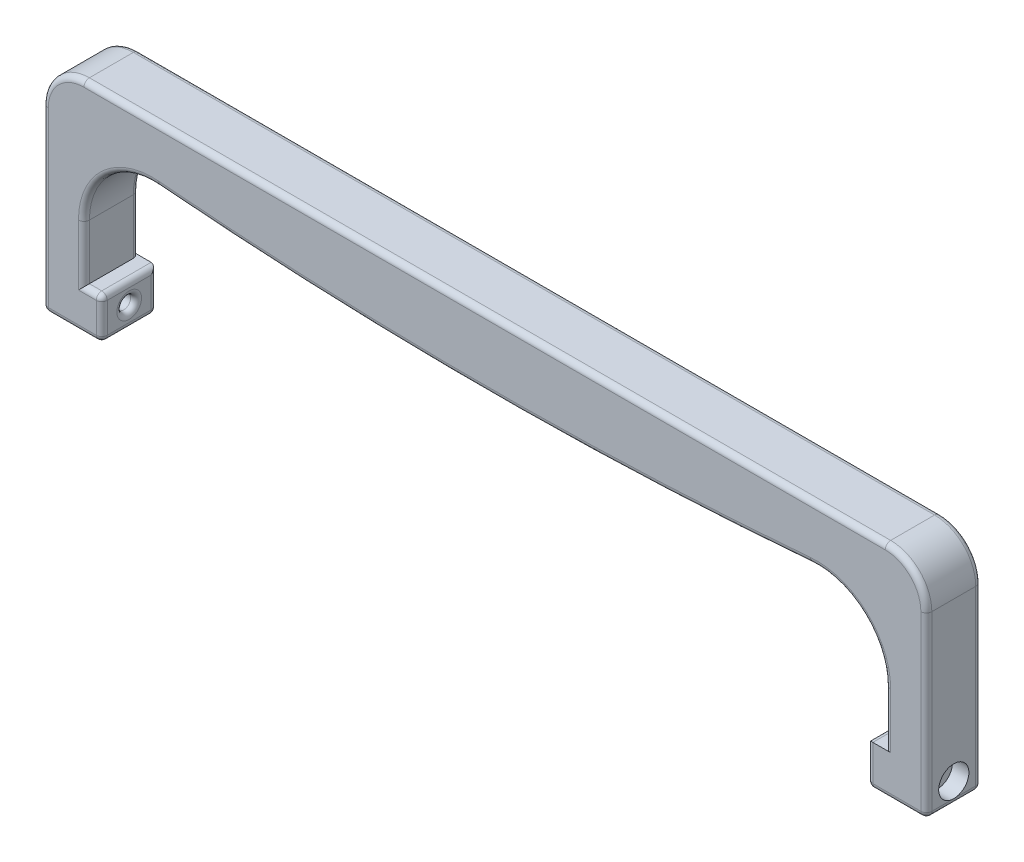
SolidWorks part; units mm, degrees
ref_plane "Ön Düzlem" through (0, 0, 0) normal (0, 0, 1) x (1, 0, 0)
ref_plane "Üst Düzlem" through (0, 0, 0) normal (0, 1, 0) x (1, 0, 0)
ref_plane "Sağ Düzlem" through (0, 0, 0) normal (1, 0, 0) x (0, 0, -1)
sketch "Sketch1" plane through (0, 0, 0) normal (0, 0, 1) x (1, 0, 0)
  line L0 (0, 0) -> (146, 0) construction
  line L1 (0, 0) -> (-146, 0) construction
  line L2 (-146, 15) -> (-146, 35.0883)
  line L3 (146, 35.0883) -> (146, 15)
  line L4 (146, 0) -> (161, 0)
  line L5 (161, 0) -> (161, 28.5778)
  line L7 (84.845, 80) -> (-146, 80)
  line L9 (-161, 28.5778) -> (-161, 0)
  line L10 (-161, 0) -> (-146, 0)
  line L11 (0, 0) -> (0, 55) construction
  line L12 (-118.9011, 60) -> (118.9011, 60) construction
  line L13 (-153.5, 0) -> (-153.5, -22.3017) construction
  line L14 (153.5, 0) -> (153.5, -21.3333) construction
  line L15 (-146, 35.0883) -> (-146, 80) construction
  line L16 (-161, 28.5778) -> (-161, 80)
  line L17 (-161, 80) -> (-146, 80)
  line L18 (84.845, 80) -> (161, 80)
  line L19 (161, 80) -> (161, 28.5778)
  line L20 (-146, 15) -> (-139.5, 15)
  line L21 (-139.5, 15) -> (-139.5, 0)
  line L22 (-139.5, 0) -> (-146, 0)
  line L23 (146, 0) -> (139.5, 0)
  line L24 (139.5, 0) -> (139.5, 15)
  line L25 (139.5, 15) -> (146, 15)
  arc A0 (-146, 35.0883) -> (-118.9011, 60) centre (-121, 35.0883) cw
  arc A1 (-118.9011, 60) -> (118.9011, 60) centre (0, 1471.2477) ccw
  arc A2 (118.9011, 60) -> (146, 35.0883) centre (121, 35.0883) cw
  dimension "D6" = 25
  dimension "D1" = 15
  dimension "D2" = 292
  dimension "D3" = 15
  dimension "D4" = 279
  dimension "D5" = 25
  dimension "D7" = 55
  dimension "D8" = 5
  dimension "D9" = 15
extrude "Boss-Extrude1" add sketch "Sketch1" along normal blind 20
fillet "Fillet7" radius 15 2 edges at (161, 80, 10) (-161, 80, 10)
sketch "Sketch5" plane through (-161, 0, 0) normal (-1, 0, 0) x (0, 0, 1)
  line L0 (10, 15) -> (10, 0) construction
  line L1 (20, 15) -> (0, 15) construction
  line L2 (20, 0) -> (0, 0) construction
  circle A0 centre (10, 7.5) radius 2.5
  dimension "D1" = 5
extrude "Cut-Extrude3" cut sketch "Sketch5" against normal through all both and the other way through all
sketch "Sketch6" plane through (-161, 0, 0) normal (-1, 0, 0) x (0, 0, 1)
  circle A0 centre (10, 7.5) radius 5.5
  dimension "D1" = 11
extrude "Cut-Extrude4" cut sketch "Sketch6" against normal blind 6
sketch "Sketch7" plane through (161, 0, 0) normal (1, 0, 0) x (0, 0, -1)
  circle A0 centre (-10, 7.5) radius 5.5 construction
  circle A1 centre (-10, 7.5) radius 5.5
extrude "Cut-Extrude5" cut sketch "Sketch7" against normal blind 6
fillet "Fillet2" radius 2 20 edges at (146, 25.0441, 20) (137.9193, 53.493, 20) (0, 55, 20) (-137.9193, 53.493, 20) (146, 25.0441, 0) (137.9193, 53.493, 0) (0, 55, 0) (-137.9193, 53.493, 0) (161, 32.5, 20) (161, 32.5, 0) (-146, 25.0441, 20) (-146, 25.0441, 0) (-161, 32.5, 0) (-161, 32.5, 20) (156.6066, 75.6066, 0) (0, 80, 0) (-156.6066, 75.6066, 0) (156.6066, 75.6066, 20) (0, 80, 20) (-156.6066, 75.6066, 20)
fillet "Fillet3" radius 2 22 edges at (149.25, 0, 0) (160.4142, 0, 0.5858) (161, 0, 10) (160.4142, 0, 19.4142) (-149.25, 0, 0) (-160.4142, 0, 0.5858) (-161, 0, 10) (-160.4142, 0, 19.4142) (139.5, 15, 10) (139.5, 7.5, 20) (139.5, 0, 10) (139.5, 7.5, 0) (139.5, 7.5, 7.5) (-139.5, 0, 10) (-139.5, 7.5, 20) (-139.5, 15, 10) (-139.5, 7.5, 0) (-139.5, 7.5, 12.5) (143.75, 15, 0) (149.25, 0, 20) (-149.25, 0, 20) (-143.75, 15, 20)
sketch "Sketch8" plane through (0, 0, -0.2) normal (0, 0, -1) x (-1, 0, 0)
  line L0 (13.5917, 71.7792) -> (12.4477, 71.7719) construction
  line L1 (12.4477, 71.7719) -> (12.4477, 70.7505) construction
  line L2 (12.4477, 70.7505) -> (11.9727, 70.2612) construction
  line L3 (11.9727, 70.2612) -> (11.6603, 69.9421) construction
  line L4 (11.6603, 69.9421) -> (10.808, 69.0802) construction
  line L5 (10.808, 69.0802) -> (9.7905, 68.0529) construction
  line L6 (9.7905, 68.0529) -> (8.6746, 66.928) construction
  line L7 (8.6746, 66.928) -> (5.8515, 64.0843) construction
  line L8 (5.8515, 64.0843) -> (7.4005, 64.1021) construction
  line L9 (7.4005, 64.1021) -> (8.367, 64.1144) construction
  line L10 (9.387, 64.425) -> (9.5549, 64.5879) construction
  line L11 (9.5549, 64.5879) -> (9.9183, 64.9488) construction
  line L12 (9.9183, 64.9488) -> (14.2886, 64.9488) construction
  line L13 (14.2886, 64.9488) -> (14.3193, 64.7681) construction
  line L14 (14.3193, 64.7681) -> (14.3331, 64.6868) construction
  line L15 (14.3331, 64.6868) -> (14.3493, 64.5913) construction
  line L16 (14.3493, 64.5913) -> (14.3653, 64.497) construction
  line L17 (14.3653, 64.497) -> (14.3784, 64.4197) construction
  line L18 (14.4551, 64.1923) -> (14.5034, 64.1326) construction
  line L19 (14.5034, 64.1326) -> (15.9518, 64.109) construction
  line L20 (15.9518, 64.109) -> (16.5084, 64.1013) construction
  line L21 (16.5084, 64.1013) -> (16.9799, 64.0975) construction
  line L22 (16.9799, 64.0975) -> (17.4007, 64.096) construction
  line L23 (17.4269, 64.1322) -> (16.7598, 67.9308) construction
  line L24 (16.7598, 67.9308) -> (16.096, 71.7092) construction
  line L25 (16.0554, 71.7873) -> (15.8667, 71.7915) construction
  line L26 (15.8667, 71.7915) -> (15.6506, 71.7939) construction
  line L27 (15.6506, 71.7939) -> (15.3964, 71.7929) construction
  line L28 (15.3964, 71.7929) -> (15.0647, 71.7899) construction
  line L29 (-30.517, 73.746) -> (-31.8816, 72.1736)
  line L30 (-31.8816, 72.1736) -> (-33.0363, 70.8497)
  line L31 (-33.0363, 70.8497) -> (-34.0807, 69.6561)
  line L32 (-34.1307, 69.6546) -> (-35.0695, 70.4608)
  line L33 (-35.0695, 70.4608) -> (-36.1096, 71.3573)
  line L34 (-36.1096, 71.3573) -> (-37.3381, 72.422)
  line L35 (-37.3381, 72.422) -> (-38.5666, 73.4878)
  line L36 (-38.5666, 73.4878) -> (-39.6068, 74.3873)
  line L37 (-39.6068, 74.3873) -> (-40.5449, 75.1969)
  line L38 (-40.651, 75.1196) -> (-40.6902, 75.0317)
  line L39 (-40.6902, 75.0317) -> (-42.2785, 71.2415)
  line L40 (-42.2785, 71.2415) -> (-44.7705, 65.2866)
  line L41 (-44.7705, 65.2866) -> (-47.6034, 58.5152)
  line L42 (-47.5883, 58.4278) -> (-46.541, 59.6299)
  line L43 (-46.541, 59.6299) -> (-45.3849, 60.9603)
  line L44 (-45.3849, 60.9603) -> (-44.0169, 62.5404)
  line L45 (-44.0169, 62.5404) -> (-42.6493, 64.1206)
  line L46 (-42.6493, 64.1206) -> (-41.4944, 65.4509)
  line L47 (-41.4944, 65.4509) -> (-40.4473, 66.6547)
  line L48 (-40.4169, 66.6556) -> (-39.4708, 65.8366)
  line L49 (-39.4708, 65.8366) -> (-38.4259, 64.9302)
  line L50 (-38.4259, 64.9302) -> (-37.1889, 63.8535)
  line L51 (-37.1889, 63.8535) -> (-35.6006, 62.472)
  line L52 (-35.6006, 62.472) -> (-34.6607, 61.6627)
  line L53 (-34.6607, 61.6627) -> (-33.9717, 61.0753)
  line L54 (-33.9037, 61.1285) -> (-30.4157, 69.4499)
  line L55 (-30.4157, 69.4499) -> (-26.9268, 77.7738)
  line L56 (-26.957, 77.8394) -> (-28.0011, 76.6423)
  line L57 (-28.0011, 76.6423) -> (-29.1532, 75.3185)
  line L58 (-30.517, 73.746) -> (-31.8816, 72.1736)
  line L59 (-31.8816, 72.1736) -> (-33.0363, 70.8497)
  line L60 (-33.0363, 70.8497) -> (-34.0807, 69.6561)
  line L61 (-34.1307, 69.6546) -> (-35.0695, 70.4608)
  line L62 (-35.0695, 70.4608) -> (-36.1096, 71.3573)
  line L63 (-36.1096, 71.3573) -> (-37.3381, 72.422)
  line L64 (-37.3381, 72.422) -> (-38.5666, 73.4878)
  line L65 (-38.5666, 73.4878) -> (-39.6068, 74.3873)
  line L66 (-39.6068, 74.3873) -> (-40.5449, 75.1969)
  line L67 (-40.651, 75.1196) -> (-40.6902, 75.0317)
  line L68 (-40.6902, 75.0317) -> (-42.2785, 71.2415)
  line L69 (-42.2785, 71.2415) -> (-44.7705, 65.2866)
  line L70 (-44.7705, 65.2866) -> (-47.6034, 58.5152)
  line L71 (-47.5883, 58.4278) -> (-46.541, 59.6299)
  line L72 (-46.541, 59.6299) -> (-45.3849, 60.9603)
  line L73 (-45.3849, 60.9603) -> (-44.0169, 62.5404)
  line L74 (-44.0169, 62.5404) -> (-42.6493, 64.1206)
  line L75 (-42.6493, 64.1206) -> (-41.4944, 65.4509)
  line L76 (-41.4944, 65.4509) -> (-40.4473, 66.6547)
  line L77 (-40.4169, 66.6556) -> (-39.4708, 65.8366)
  line L78 (-39.4708, 65.8366) -> (-38.4259, 64.9302)
  line L79 (-38.4259, 64.9302) -> (-37.1889, 63.8535)
  line L80 (-37.1889, 63.8535) -> (-35.6006, 62.472)
  line L81 (-35.6006, 62.472) -> (-34.6607, 61.6627)
  line L82 (-34.6607, 61.6627) -> (-33.9717, 61.0753)
  line L83 (-33.9037, 61.1285) -> (-30.4157, 69.4499)
  line L84 (-30.4157, 69.4499) -> (-26.9268, 77.7738)
  line L85 (-26.957, 77.8394) -> (-28.0011, 76.6423)
  line L86 (-28.0011, 76.6423) -> (-29.1532, 75.3185)
  line L87 (15.0647, 71.7899) -> (14.5937, 71.7862) construction
  line L88 (14.5937, 71.7862) -> (14.0781, 71.7825) construction
  line L89 (-3.5813, 71.7993) -> (-3.5813, 70.2877) construction
  line L90 (-3.5813, 70.2877) -> (-4.878, 67.2503) construction
  line L91 (-4.878, 67.2503) -> (-5.3764, 66.0823) construction
  line L92 (-5.3764, 66.0823) -> (-5.799, 65.0911) construction
  line L93 (-5.799, 65.0911) -> (-6.1772, 64.2033) construction
  line L94 (-6.1772, 64.2033) -> (-6.1925, 64.165) construction
  line L95 (-5.772, 64.121) -> (-5.0497, 64.1248) construction
  line L96 (-5.0497, 64.1248) -> (-3.8891, 64.1326) construction
  line L97 (-3.8891, 64.1326) -> (-3.7553, 64.2034) construction
  line L98 (-3.4372, 64.4881) -> (-3.4095, 64.5458) construction
  line L99 (-3.4095, 64.5458) -> (-3.3182, 64.7528) construction
  line L100 (-3.3182, 64.7528) -> (-3.2109, 64.9986) construction
  line L101 (-25.1946, 71.8011) -> (-25.2279, 70.3122)
  line L102 (-25.2279, 70.3122) -> (-26.5297, 67.2491)
  line L103 (-26.5297, 67.2491) -> (-27.0298, 66.0723)
  line L104 (-27.0298, 66.0723) -> (-27.4531, 65.0758)
  line L105 (-27.4531, 65.0758) -> (-27.8337, 64.1795)
  line L106 (-27.8337, 64.1795) -> (-27.8452, 64.1516)
  line L107 (-27.8323, 64.1321) -> (-27.6149, 64.1255)
  line L108 (-27.6149, 64.1255) -> (-27.2782, 64.1221)
  line L109 (-27.2782, 64.1221) -> (-26.6314, 64.1249)
  line L110 (-26.6314, 64.1249) -> (-25.4039, 64.1326)
  line L111 (-25.4039, 64.1326) -> (-25.2507, 64.2078)
  line L112 (-24.9429, 64.4922) -> (-24.7356, 64.9493)
  line L113 (-24.7356, 64.9493) -> (-24.454, 65.5884)
  line L114 (-24.454, 65.5884) -> (-24.0391, 66.5517)
  line L115 (-24.0391, 66.5517) -> (-23.6994, 67.3423)
  line L116 (-23.6994, 67.3423) -> (-23.4108, 68.008)
  line L117 (-23.4108, 68.008) -> (-23.1493, 68.608)
  line L118 (-23.1311, 68.6086) -> (-22.8358, 67.9695)
  line L119 (-22.8358, 67.9695) -> (-22.51, 67.2606)
  line L120 (-22.51, 67.2606) -> (-22.126, 66.4185)
  line L121 (-22.126, 66.4185) -> (-21.6201, 65.3102)
  line L122 (-21.6201, 65.3102) -> (-21.3228, 64.6737)
  line L123 (-21.3228, 64.6737) -> (-21.1139, 64.2395)
  line L124 (-20.5132, 64.1339) -> (-19.839, 64.1326)
  line L125 (-19.839, 64.1326) -> (-18.6872, 64.1326)
  line L126 (-18.6872, 64.1326) -> (-18.5174, 64.2246)
  line L127 (-18.2242, 64.5066) -> (-16.7137, 68.0459)
  line L128 (-16.7137, 68.0459) -> (-15.2225, 71.542)
  line L129 (-15.5907, 71.7982) -> (-16.3489, 71.7941)
  line L130 (-16.3489, 71.7941) -> (-17.5633, 71.7859)
  line L131 (-17.5633, 71.7859) -> (-17.6955, 71.7203)
  line L132 (-18.2461, 70.9566) -> (-18.8059, 69.6317)
  line L133 (-18.8059, 69.6317) -> (-19.0984, 68.9368)
  line L134 (-19.0984, 68.9368) -> (-19.3491, 68.3462)
  line L135 (-19.3491, 68.3462) -> (-19.5732, 67.821)
  line L136 (-19.8037, 67.8199) -> (-20.0598, 68.3812)
  line L137 (-20.0598, 68.3812) -> (-20.3462, 69.0103)
  line L138 (-20.3462, 69.0103) -> (-20.6822, 69.7509)
  line L139 (-20.6822, 69.7509) -> (-21.1251, 70.7235)
  line L140 (-21.1251, 70.7235) -> (-21.3873, 71.2842)
  line L141 (-21.3873, 71.2842) -> (-21.5702, 71.6613)
  line L142 (-22.3255, 71.7876) -> (-23.4481, 71.7935)
  line L143 (-23.4481, 71.7935) -> (-25.1946, 71.8011)
  line L144 (-25.1946, 71.8011) -> (-25.2279, 70.3122)
  line L145 (-25.2279, 70.3122) -> (-26.5297, 67.2491)
  line L146 (-26.5297, 67.2491) -> (-27.0298, 66.0723)
  line L147 (-27.0298, 66.0723) -> (-27.4531, 65.0758)
  line L148 (-27.4531, 65.0758) -> (-27.8337, 64.1795)
  line L149 (-27.8337, 64.1795) -> (-27.8452, 64.1516)
  line L150 (-27.8323, 64.1321) -> (-27.6149, 64.1255)
  line L151 (-27.6149, 64.1255) -> (-27.2782, 64.1221)
  line L152 (-27.2782, 64.1221) -> (-26.6314, 64.1249)
  line L153 (-26.6314, 64.1249) -> (-25.4039, 64.1326)
  line L154 (-25.4039, 64.1326) -> (-25.2507, 64.2078)
  line L155 (-24.9429, 64.4922) -> (-24.7356, 64.9493)
  line L156 (-24.7356, 64.9493) -> (-24.454, 65.5884)
  line L157 (-24.454, 65.5884) -> (-24.0391, 66.5517)
  line L158 (-24.0391, 66.5517) -> (-23.6994, 67.3423)
  line L159 (-23.6994, 67.3423) -> (-23.4108, 68.008)
  line L160 (-23.4108, 68.008) -> (-23.1493, 68.608)
  line L161 (-23.1311, 68.6086) -> (-22.8358, 67.9695)
  line L162 (-22.8358, 67.9695) -> (-22.51, 67.2606)
  line L163 (-22.51, 67.2606) -> (-22.126, 66.4185)
  line L164 (-22.126, 66.4185) -> (-21.6201, 65.3102)
  line L165 (-21.6201, 65.3102) -> (-21.3228, 64.6737)
  line L166 (-21.3228, 64.6737) -> (-21.1139, 64.2395)
  line L167 (-20.5132, 64.1339) -> (-19.839, 64.1326)
  line L168 (-19.839, 64.1326) -> (-18.6872, 64.1326)
  line L169 (-18.6872, 64.1326) -> (-18.5174, 64.2246)
  line L170 (-18.2242, 64.5066) -> (-16.7137, 68.0459)
  line L171 (-16.7137, 68.0459) -> (-15.2225, 71.542)
  line L172 (-15.5907, 71.7982) -> (-16.3489, 71.7941)
  line L173 (-16.3489, 71.7941) -> (-17.5633, 71.7859)
  line L174 (-17.5633, 71.7859) -> (-17.6955, 71.7203)
  line L175 (-18.2461, 70.9566) -> (-18.8059, 69.6317)
  line L176 (-18.8059, 69.6317) -> (-19.0984, 68.9368)
  line L177 (-19.0984, 68.9368) -> (-19.3491, 68.3462)
  line L178 (-19.3491, 68.3462) -> (-19.5732, 67.821)
  line L179 (-19.8037, 67.8199) -> (-20.0598, 68.3812)
  line L180 (-20.0598, 68.3812) -> (-20.3462, 69.0103)
  line L181 (-20.3462, 69.0103) -> (-20.6822, 69.7509)
  line L182 (-20.6822, 69.7509) -> (-21.1251, 70.7235)
  line L183 (-21.1251, 70.7235) -> (-21.3873, 71.2842)
  line L184 (-21.3873, 71.2842) -> (-21.5702, 71.6613)
  line L185 (-22.3255, 71.7876) -> (-23.4481, 71.7935)
  line L186 (-23.4481, 71.7935) -> (-25.1946, 71.8011)
  line L187 (-3.2109, 64.9986) -> (-3.0917, 65.2745) construction
  line L188 (-3.0917, 65.2745) -> (-2.902, 65.7249) construction
  line L189 (-2.7144, 66.2822) -> (-2.5766, 66.8086) construction
  line L190 (-2.5766, 66.8086) -> (-2.3647, 67.6381) construction
  line L191 (-2.3647, 67.6381) -> (-2.3424, 67.4909) construction
  line L192 (-2.3424, 67.4909) -> (-2.1759, 66.4174) construction
  line L193 (-2.1759, 66.4174) -> (-2.001, 65.3432) construction
  line L194 (-2.001, 65.3432) -> (-1.8277, 64.3062) construction
  line L195 (-1.1942, 64.1215) -> (-0.3702, 64.1243) construction
  line L196 (-0.3702, 64.1243) -> (0.4121, 64.1309) construction
  line L197 (1.039, 64.263) -> (1.3895, 64.5936) construction
  line L198 (1.3895, 64.5936) -> (1.8582, 65.0459) construction
  line L199 (1.8582, 65.0459) -> (2.5199, 65.6965) construction
  line L200 (2.5199, 65.6965) -> (3.0795, 66.2488) construction
  line L201 (3.0795, 66.2488) -> (3.5516, 66.7128) construction
  line L202 (3.5516, 66.7128) -> (3.9794, 67.1323) construction
  line L203 (3.9853, 67.1271) -> (3.8229, 66.7398) construction
  line L204 (3.8229, 66.7398) -> (3.6425, 66.3114) construction
  line L205 (3.6425, 66.3114) -> (3.4271, 65.8037) construction
  line L206 (3.4271, 65.8037) -> (3.2103, 65.2905) construction
  line L207 (3.2103, 65.2905) -> (3.0253, 64.8447) construction
  line L208 (3.0253, 64.8447) -> (2.8673, 64.4584) construction
  line L209 (3.5576, 64.1231) -> (4.1957, 64.1256) construction
  line L210 (4.1957, 64.1256) -> (5.338, 64.1326) construction
  line L211 (5.338, 64.1326) -> (6.9661, 67.9543) construction
  line L212 (6.9661, 67.9543) -> (7.5905, 69.4206) construction
  line L213 (7.5905, 69.4206) -> (8.116, 70.6572) construction
  line L214 (8.116, 70.6572) -> (8.5922, 71.7787) construction
  line L215 (8.589, 71.7943) -> (8.1915, 71.7958) construction
  line L216 (8.1915, 71.7958) -> (7.7488, 71.7961) construction
  line L217 (7.7488, 71.7961) -> (7.2229, 71.7939) construction
  line L218 (7.2229, 71.7939) -> (5.8515, 71.7859) construction
  line L219 (5.8515, 71.7859) -> (5.7177, 71.7216) construction
  line L220 (5.5902, 71.6332) -> (5.1182, 71.1787) construction
  line L221 (5.1182, 71.1787) -> (4.4076, 70.4805) construction
  line L222 (4.4076, 70.4805) -> (3.1287, 69.2066) construction
  line L223 (3.1287, 69.2066) -> (2.1872, 68.2687) construction
  line L224 (2.1872, 68.2687) -> (1.3947, 67.4836) construction
  line L225 (1.3947, 67.4836) -> (0.6812, 66.7793) construction
  line L226 (0.6716, 66.804) -> (0.5984, 67.2298) construction
  line L227 (0.5984, 67.2298) -> (0.516, 67.7065) construction
  line L228 (0.516, 67.7065) -> (0.418, 68.2674) construction
  line L229 (0.418, 68.2674) -> (0.2912, 69.0089) construction
  line L230 (0.2912, 69.0089) -> (0.1961, 69.6063) construction
  line L231 (0.1961, 69.6063) -> (0.1213, 70.132) construction
  line L232 (0.1213, 70.132) -> (0.0574, 70.6486) construction
  line L233 (0.0574, 70.6486) -> (0.016, 71.0105) construction
  line L234 (0.016, 71.0105) -> (-0.0215, 71.334) construction
  line L235 (-0.0215, 71.334) -> (-0.0534, 71.6066) construction
  line L236 (-0.0534, 71.6066) -> (-0.0635, 71.6855) construction
  line L237 (-0.0635, 71.6855) -> (-0.0791, 71.7993) construction
  line L238 (-0.0791, 71.7993) -> (-3.5813, 71.7993) construction
  line L239 (13.5917, 71.7792) -> (12.4477, 71.7719)
  line L240 (12.4477, 71.7719) -> (12.4477, 70.7505)
  line L241 (12.4477, 70.7505) -> (11.9727, 70.2612)
  line L242 (11.9727, 70.2612) -> (11.6603, 69.9421)
  line L243 (11.6603, 69.9421) -> (10.808, 69.0802)
  line L244 (10.808, 69.0802) -> (9.7905, 68.0529)
  line L245 (9.7905, 68.0529) -> (8.6746, 66.928)
  line L246 (8.6746, 66.928) -> (5.8515, 64.0843)
  line L247 (5.8515, 64.0843) -> (7.4005, 64.1021)
  line L248 (7.4005, 64.1021) -> (8.367, 64.1144)
  line L249 (9.387, 64.425) -> (9.5549, 64.5879)
  line L250 (9.5549, 64.5879) -> (9.9183, 64.9488)
  line L251 (9.9183, 64.9488) -> (14.2886, 64.9488)
  line L252 (14.2886, 64.9488) -> (14.3193, 64.7681)
  line L253 (14.3193, 64.7681) -> (14.3331, 64.6868)
  line L254 (14.3331, 64.6868) -> (14.3493, 64.5913)
  line L255 (14.3493, 64.5913) -> (14.3653, 64.497)
  line L256 (14.3653, 64.497) -> (14.3784, 64.4197)
  line L257 (14.4551, 64.1923) -> (14.5034, 64.1326)
  line L258 (14.5034, 64.1326) -> (15.9518, 64.109)
  line L259 (15.9518, 64.109) -> (16.5084, 64.1013)
  line L260 (16.5084, 64.1013) -> (16.9799, 64.0975)
  line L261 (16.9799, 64.0975) -> (17.4007, 64.096)
  line L262 (17.4269, 64.1322) -> (16.7598, 67.9308)
  line L263 (16.7598, 67.9308) -> (16.096, 71.7092)
  line L264 (16.0554, 71.7873) -> (15.8667, 71.7915)
  line L265 (15.8667, 71.7915) -> (15.6506, 71.7939)
  line L266 (15.6506, 71.7939) -> (15.3964, 71.7929)
  line L267 (15.3964, 71.7929) -> (15.0647, 71.7899)
  line L268 (15.0647, 71.7899) -> (14.5937, 71.7862)
  line L269 (14.5937, 71.7862) -> (14.0781, 71.7825)
  line L270 (-3.5813, 71.7993) -> (-3.5813, 70.2877)
  line L271 (-3.5813, 70.2877) -> (-4.878, 67.2503)
  line L272 (-4.878, 67.2503) -> (-5.3764, 66.0823)
  line L273 (-5.3764, 66.0823) -> (-5.799, 65.0911)
  line L274 (-5.799, 65.0911) -> (-6.1772, 64.2033)
  line L275 (-6.1772, 64.2033) -> (-6.1925, 64.165)
  line L276 (-5.772, 64.121) -> (-5.0497, 64.1248)
  line L277 (-5.0497, 64.1248) -> (-3.8891, 64.1326)
  line L278 (-3.8891, 64.1326) -> (-3.7553, 64.2034)
  line L279 (-3.4372, 64.4881) -> (-3.4095, 64.5458)
  line L280 (-3.4095, 64.5458) -> (-3.3182, 64.7528)
  line L281 (-3.3182, 64.7528) -> (-3.2109, 64.9986)
  line L282 (-3.2109, 64.9986) -> (-3.0917, 65.2745)
  line L283 (-3.0917, 65.2745) -> (-2.902, 65.7249)
  line L284 (-2.7144, 66.2822) -> (-2.5766, 66.8086)
  line L285 (-2.5766, 66.8086) -> (-2.3647, 67.6381)
  line L286 (-2.3647, 67.6381) -> (-2.3424, 67.4909)
  line L287 (-2.3424, 67.4909) -> (-2.1759, 66.4174)
  line L288 (-2.1759, 66.4174) -> (-2.001, 65.3432)
  line L289 (-2.001, 65.3432) -> (-1.8277, 64.3062)
  line L290 (-1.1942, 64.1215) -> (-0.3702, 64.1243)
  line L291 (-0.3702, 64.1243) -> (0.4121, 64.1309)
  line L292 (1.039, 64.263) -> (1.3895, 64.5936)
  line L293 (1.3895, 64.5936) -> (1.8582, 65.0459)
  line L294 (1.8582, 65.0459) -> (2.5199, 65.6965)
  line L295 (2.5199, 65.6965) -> (3.0795, 66.2488)
  line L296 (3.0795, 66.2488) -> (3.5516, 66.7128)
  line L297 (3.5516, 66.7128) -> (3.9794, 67.1323)
  line L298 (3.9853, 67.1271) -> (3.8229, 66.7398)
  line L299 (3.8229, 66.7398) -> (3.6425, 66.3114)
  line L300 (3.6425, 66.3114) -> (3.4271, 65.8037)
  line L301 (3.4271, 65.8037) -> (3.2103, 65.2905)
  line L302 (3.2103, 65.2905) -> (3.0253, 64.8447)
  line L303 (3.0253, 64.8447) -> (2.8673, 64.4584)
  line L304 (3.5576, 64.1231) -> (4.1957, 64.1256)
  line L305 (4.1957, 64.1256) -> (5.338, 64.1326)
  line L306 (5.338, 64.1326) -> (6.9661, 67.9543)
  line L307 (6.9661, 67.9543) -> (7.5905, 69.4206)
  line L308 (7.5905, 69.4206) -> (8.116, 70.6572)
  line L309 (8.116, 70.6572) -> (8.5922, 71.7787)
  line L310 (8.589, 71.7943) -> (8.1915, 71.7958)
  line L311 (8.1915, 71.7958) -> (7.7488, 71.7961)
  line L312 (7.7488, 71.7961) -> (7.2229, 71.7939)
  line L313 (7.2229, 71.7939) -> (5.8515, 71.7859)
  line L314 (5.8515, 71.7859) -> (5.7177, 71.7216)
  line L315 (5.5902, 71.6332) -> (5.1182, 71.1787)
  line L316 (5.1182, 71.1787) -> (4.4076, 70.4805)
  line L317 (4.4076, 70.4805) -> (3.1287, 69.2066)
  line L318 (3.1287, 69.2066) -> (2.1872, 68.2687)
  line L319 (2.1872, 68.2687) -> (1.3947, 67.4836)
  line L320 (1.3947, 67.4836) -> (0.6812, 66.7793)
  line L321 (0.6716, 66.804) -> (0.5984, 67.2298)
  line L322 (0.5984, 67.2298) -> (0.516, 67.7065)
  line L323 (0.516, 67.7065) -> (0.418, 68.2674)
  line L324 (0.418, 68.2674) -> (0.2912, 69.0089)
  line L325 (0.2912, 69.0089) -> (0.1961, 69.6063)
  line L326 (0.1961, 69.6063) -> (0.1213, 70.132)
  line L327 (0.1213, 70.132) -> (0.0574, 70.6486)
  line L328 (0.0574, 70.6486) -> (0.016, 71.0105)
  line L329 (0.016, 71.0105) -> (-0.0215, 71.334)
  line L330 (-0.0215, 71.334) -> (-0.0534, 71.6066)
  line L331 (-0.0534, 71.6066) -> (-0.0635, 71.6855)
  line L332 (-0.0635, 71.6855) -> (-0.0791, 71.7993)
  line L333 (-0.0791, 71.7993) -> (-3.5813, 71.7993)
  line L334 (11.7959, 66.7669) -> (14.007, 66.7885)
  line L335 (14.007, 66.7885) -> (13.6567, 68.706)
  line L336 (13.6567, 68.706) -> (11.7959, 66.7669)
  line L337 (31.1127, 71.716) -> (31.0101, 71.4717) construction
  line L338 (31.0101, 71.4717) -> (30.8919, 71.1891) construction
  line L339 (30.8919, 71.1891) -> (30.7564, 70.8627) construction
  line L340 (30.7564, 70.8627) -> (30.6188, 70.5305) construction
  line L341 (30.6188, 70.5305) -> (30.494, 70.2299) construction
  line L342 (30.494, 70.2299) -> (30.389, 69.9778) construction
  line L343 (30.389, 69.9778) -> (30.3528, 69.8924) construction
  line L344 (30.3528, 69.8924) -> (30.2981, 69.765) construction
  line L345 (30.2981, 69.765) -> (33.0892, 69.7789) construction
  line L346 (33.0892, 69.7789) -> (33.5254, 70.769) construction
  line L347 (33.5254, 70.769) -> (33.6926, 71.1501) construction
  line L348 (33.6926, 71.1501) -> (33.8335, 71.4742) construction
  line L349 (33.8335, 71.4742) -> (33.9586, 71.7637) construction
  line L350 (33.9541, 71.7874) -> (33.55, 71.7934) construction
  line L351 (20.5107, 71.7737) -> (20.48, 70.2553)
  line L352 (20.48, 70.2553) -> (19.1898, 67.2207)
  line L353 (19.1898, 67.2207) -> (18.6941, 66.0538)
  line L354 (18.6941, 66.0538) -> (18.2747, 65.0636)
  line L355 (18.2747, 65.0636) -> (17.8995, 64.1761)
  line L356 (17.9105, 64.1065) -> (18.3839, 64.099)
  line L357 (18.3839, 64.099) -> (19.1945, 64.095)
  line L358 (19.1945, 64.095) -> (21.4558, 64.099)
  line L359 (21.4558, 64.099) -> (25.0382, 64.1069)
  line L360 (25.0382, 64.1069) -> (25.3109, 64.1792)
  line L361 (27.8496, 66.2627) -> (28.5848, 68.0031)
  line L362 (28.5848, 68.0031) -> (29.34, 69.7964)
  line L363 (28.4498, 71.6967) -> (28.2493, 71.7585)
  line L364 (28.2493, 71.7585) -> (20.5107, 71.7737)
  line L365 (20.5107, 71.7737) -> (20.48, 70.2553)
  line L366 (20.48, 70.2553) -> (19.1898, 67.2207)
  line L367 (19.1898, 67.2207) -> (18.6941, 66.0538)
  line L368 (18.6941, 66.0538) -> (18.2747, 65.0636)
  line L369 (18.2747, 65.0636) -> (17.8995, 64.1761)
  line L370 (17.9105, 64.1065) -> (18.3839, 64.099)
  line L371 (18.3839, 64.099) -> (19.1945, 64.095)
  line L372 (19.1945, 64.095) -> (21.4558, 64.099)
  line L373 (21.4558, 64.099) -> (25.0382, 64.1069)
  line L374 (25.0382, 64.1069) -> (25.3109, 64.1792)
  line L375 (27.8496, 66.2627) -> (28.5848, 68.0031)
  line L376 (28.5848, 68.0031) -> (29.34, 69.7964)
  line L377 (28.4498, 71.6967) -> (28.2493, 71.7585)
  line L378 (28.2493, 71.7585) -> (20.5107, 71.7737)
  line L379 (33.55, 71.7934) -> (33.0969, 71.7978) construction
  line L380 (33.0969, 71.7978) -> (32.5586, 71.7993) construction
  line L381 (32.5586, 71.7993) -> (31.697, 71.7982) construction
  line L382 (30.0275, 69.0163) -> (30.0037, 68.956) construction
  line L383 (30.0037, 68.956) -> (29.9841, 68.9084) construction
  line L384 (29.9841, 68.9084) -> (29.6944, 68.2257) construction
  line L385 (29.6944, 68.2257) -> (29.3676, 67.4563) construction
  line L386 (29.3676, 67.4563) -> (28.9841, 66.5544) construction
  line L387 (28.9841, 66.5544) -> (28.6015, 65.6523) construction
  line L388 (28.6015, 65.6523) -> (28.277, 64.8825) construction
  line L389 (28.277, 64.8825) -> (27.9901, 64.1989) construction
  line L390 (27.9749, 64.1509) -> (27.9614, 64.089) construction
  line L391 (27.9614, 64.089) -> (30.3633, 64.1058) construction
  line L392 (30.3633, 64.1058) -> (30.5273, 64.1816) construction
  line L393 (31.1381, 65.0528) -> (31.8509, 66.7022) construction
  line L394 (31.8509, 66.7022) -> (32.2224, 67.5662) construction
  line L395 (32.2224, 67.5662) -> (32.5375, 68.2991) construction
  line L396 (32.5375, 68.2991) -> (32.8197, 68.9559) construction
  line L397 (32.8197, 68.9559) -> (32.8309, 68.9828) construction
  line L398 (32.8185, 69.0018) -> (32.5559, 69.0095) construction
  line L399 (32.5559, 69.0095) -> (32.163, 69.0149) construction
  line L400 (32.163, 69.0149) -> (31.4359, 69.0163) construction
  line L401 (31.4359, 69.0163) -> (30.0275, 69.0163) construction
  line L402 (31.1127, 71.716) -> (31.0101, 71.4717)
  line L403 (31.0101, 71.4717) -> (30.8919, 71.1891)
  line L404 (30.8919, 71.1891) -> (30.7564, 70.8627)
  line L405 (30.7564, 70.8627) -> (30.6188, 70.5305)
  line L406 (30.6188, 70.5305) -> (30.494, 70.2299)
  line L407 (30.494, 70.2299) -> (30.389, 69.9778)
  line L408 (30.389, 69.9778) -> (30.3528, 69.8924)
  line L409 (30.3528, 69.8924) -> (30.2981, 69.765)
  line L410 (30.2981, 69.765) -> (33.0892, 69.7789)
  line L411 (33.0892, 69.7789) -> (33.5254, 70.769)
  line L412 (33.5254, 70.769) -> (33.6926, 71.1501)
  line L413 (33.6926, 71.1501) -> (33.8335, 71.4742)
  line L414 (33.8335, 71.4742) -> (33.9586, 71.7637)
  line L415 (33.9541, 71.7874) -> (33.55, 71.7934)
  line L416 (33.55, 71.7934) -> (33.0969, 71.7978)
  line L417 (33.0969, 71.7978) -> (32.5586, 71.7993)
  line L418 (32.5586, 71.7993) -> (31.697, 71.7982)
  line L419 (30.0275, 69.0163) -> (30.0037, 68.956)
  line L420 (30.0037, 68.956) -> (29.9841, 68.9084)
  line L421 (29.9841, 68.9084) -> (29.6944, 68.2257)
  line L422 (29.6944, 68.2257) -> (29.3676, 67.4563)
  line L423 (29.3676, 67.4563) -> (28.9841, 66.5544)
  line L424 (28.9841, 66.5544) -> (28.6015, 65.6523)
  line L425 (28.6015, 65.6523) -> (28.277, 64.8825)
  line L426 (28.277, 64.8825) -> (27.9901, 64.1989)
  line L427 (27.9749, 64.1509) -> (27.9614, 64.089)
  line L428 (27.9614, 64.089) -> (30.3633, 64.1058)
  line L429 (30.3633, 64.1058) -> (30.5273, 64.1816)
  line L430 (31.1381, 65.0528) -> (31.8509, 66.7022)
  line L431 (31.8509, 66.7022) -> (32.2224, 67.5662)
  line L432 (32.2224, 67.5662) -> (32.5375, 68.2991)
  line L433 (32.5375, 68.2991) -> (32.8197, 68.9559)
  line L434 (32.8197, 68.9559) -> (32.8309, 68.9828)
  line L435 (32.8185, 69.0018) -> (32.5559, 69.0095)
  line L436 (32.5559, 69.0095) -> (32.163, 69.0149)
  line L437 (32.163, 69.0149) -> (31.4359, 69.0163)
  line L438 (31.4359, 69.0163) -> (30.0275, 69.0163)
  line L439 (21.9151, 66.119) -> (24.6899, 66.1137)
  line L440 (24.6899, 66.1137) -> (24.943, 66.2197)
  line L441 (24.943, 66.2197) -> (26.4633, 69.6104)
  line L442 (26.4633, 69.6104) -> (26.3013, 69.7765)
  line L443 (26.3013, 69.7765) -> (23.0686, 69.7923)
  line L444 (23.0686, 69.7923) -> (21.6091, 66.3272)
  line L445 (21.6091, 66.3272) -> (21.6889, 66.1423)
  line L446 (21.6889, 66.1423) -> (21.9151, 66.119)
  line L447 (35.7246, 66.0912) -> (38.2307, 66.073)
  line L448 (38.2307, 66.073) -> (39.2248, 68.4463)
  line L449 (39.2248, 68.4463) -> (40.361, 67.0297)
  line L450 (40.361, 67.0297) -> (41.4089, 69.5268)
  line L451 (41.4089, 69.5268) -> (41.3324, 69.769)
  line L452 (41.3324, 69.769) -> (36.9646, 69.7923)
  line L453 (36.9646, 69.7923) -> (35.4959, 66.2594)
  line L454 (35.4959, 66.2594) -> (35.7246, 66.0912)
  line L455 (-13.5976, 66.3764) -> (-12.1646, 69.7923)
  line L456 (-12.1646, 69.7923) -> (-7.8655, 69.7761)
  line L457 (-7.8655, 69.7761) -> (-7.7361, 69.5699)
  line L458 (-7.7361, 69.5699) -> (-9.0708, 66.422)
  line L459 (-9.0708, 66.422) -> (-9.4391, 66.1467)
  line L460 (-9.4391, 66.1467) -> (-13.4849, 66.1262)
  line L461 (-13.4849, 66.1262) -> (-13.5976, 66.3764)
  line L470 (34.0021, 69.3718) -> (33.4015, 67.9726)
  line L471 (33.4015, 67.9726) -> (33.0684, 67.1868)
  line L472 (33.0684, 67.1868) -> (32.7805, 66.4986)
  line L473 (32.7805, 66.4986) -> (32.5363, 65.9079)
  line L474 (33.9889, 64.081) -> (34.654, 64.0728)
  line L475 (34.654, 64.0728) -> (35.528, 64.0669)
  line L476 (35.528, 64.0669) -> (36.7006, 64.0648)
  line L477 (36.7006, 64.0648) -> (39.3814, 64.0639)
  line L478 (39.3814, 64.0639) -> (40.1687, 63.0333)
  line L479 (40.1687, 63.0333) -> (40.4717, 62.6375)
  line L480 (40.4717, 62.6375) -> (40.7293, 62.3026)
  line L481 (40.7293, 62.3026) -> (40.9608, 62.0028)
  line L482 (40.9872, 61.998) -> (41.5253, 63.2658)
  line L483 (41.5253, 63.2658) -> (42.038, 64.476)
  line L484 (42.0041, 64.8145) -> (41.905, 64.9495)
  line L485 (41.905, 64.9495) -> (42.1819, 65.2395)
  line L486 (42.7337, 66.0299) -> (43.5106, 67.8299)
  line L487 (43.5106, 67.8299) -> (44.2647, 69.5876)
  line L488 (43.3643, 71.7523) -> (43.1545, 71.8115)
  line L489 (43.1545, 71.8115) -> (40.2109, 71.8158)
  line L490 (40.2109, 71.8158) -> (39.0683, 71.8157)
  line L491 (39.0683, 71.8157) -> (38.0731, 71.8119)
  line L492 (38.0731, 71.8119) -> (37.2183, 71.806)
  line L493 (34.0021, 69.3718) -> (33.4015, 67.9726)
  line L494 (33.4015, 67.9726) -> (33.0684, 67.1868)
  line L495 (33.0684, 67.1868) -> (32.7805, 66.4986)
  line L496 (32.7805, 66.4986) -> (32.5363, 65.9079)
  line L497 (33.9889, 64.081) -> (34.654, 64.0728)
  line L498 (34.654, 64.0728) -> (35.528, 64.0669)
  line L499 (35.528, 64.0669) -> (36.7006, 64.0648)
  line L500 (36.7006, 64.0648) -> (39.3814, 64.0639)
  line L501 (39.3814, 64.0639) -> (40.1687, 63.0333)
  line L502 (40.1687, 63.0333) -> (40.4717, 62.6375)
  line L503 (40.4717, 62.6375) -> (40.7293, 62.3026)
  line L504 (40.7293, 62.3026) -> (40.9608, 62.0028)
  line L505 (40.9872, 61.998) -> (41.5253, 63.2658)
  line L506 (41.5253, 63.2658) -> (42.038, 64.476)
  line L507 (42.0041, 64.8145) -> (41.905, 64.9495)
  line L508 (41.905, 64.9495) -> (42.1819, 65.2395)
  line L509 (42.7337, 66.0299) -> (43.5106, 67.8299)
  line L510 (43.5106, 67.8299) -> (44.2647, 69.5876)
  line L511 (43.3643, 71.7523) -> (43.1545, 71.8115)
  line L512 (43.1545, 71.8115) -> (40.2109, 71.8158)
  line L513 (40.2109, 71.8158) -> (39.0683, 71.8157)
  line L514 (39.0683, 71.8157) -> (38.0731, 71.8119)
  line L515 (38.0731, 71.8119) -> (37.2183, 71.806)
  line L516 (-14.9281, 69.8642) -> (-15.1723, 69.294)
  line L517 (-15.1723, 69.294) -> (-15.4556, 68.629)
  line L518 (-15.4556, 68.629) -> (-15.7789, 67.8656)
  line L519 (-15.7789, 67.8656) -> (-16.3838, 66.4229)
  line L520 (-14.9745, 64.113) -> (-14.2012, 64.107)
  line L521 (-14.2012, 64.107) -> (-12.2916, 64.1058)
  line L522 (-12.2916, 64.1058) -> (-9.1607, 64.1058)
  line L523 (-9.1607, 64.1058) -> (-8.8727, 64.181)
  line L524 (-6.449, 66.0116) -> (-5.6577, 67.8497)
  line L525 (-5.6577, 67.8497) -> (-4.8818, 69.6631)
  line L526 (-5.7223, 71.6965) -> (-5.9228, 71.7582)
  line L527 (-5.9228, 71.7582) -> (-8.9868, 71.763)
  line L528 (-8.9868, 71.763) -> (-10.5451, 71.7639)
  line L529 (-10.5451, 71.7639) -> (-11.4553, 71.7596)
  line L530 (-11.4553, 71.7596) -> (-12.0579, 71.7516)
  line L531 (-14.9281, 69.8642) -> (-15.1723, 69.294)
  line L532 (-15.1723, 69.294) -> (-15.4556, 68.629)
  line L533 (-15.4556, 68.629) -> (-15.7789, 67.8656)
  line L534 (-15.7789, 67.8656) -> (-16.3838, 66.4229)
  line L535 (-14.9745, 64.113) -> (-14.2012, 64.107)
  line L536 (-14.2012, 64.107) -> (-12.2916, 64.1058)
  line L537 (-12.2916, 64.1058) -> (-9.1607, 64.1058)
  line L538 (-9.1607, 64.1058) -> (-8.8727, 64.181)
  line L539 (-6.449, 66.0116) -> (-5.6577, 67.8497)
  line L540 (-5.6577, 67.8497) -> (-4.8818, 69.6631)
  line L541 (-5.7223, 71.6965) -> (-5.9228, 71.7582)
  line L542 (-5.9228, 71.7582) -> (-8.9868, 71.763)
  line L543 (-8.9868, 71.763) -> (-10.5451, 71.7639)
  line L544 (-10.5451, 71.7639) -> (-11.4553, 71.7596)
  line L545 (-11.4553, 71.7596) -> (-12.0579, 71.7516)
  arc A0 (13.5917, 71.7792) -> (14.0781, 71.7825) centre (8.9063, 808.7713) ccw construction
  arc A1 (8.367, 64.1144) -> (8.7435, 64.1251) centre (8.1838, 77.2208) ccw construction
  arc A2 (8.7435, 64.1251) -> (8.9516, 64.1413) centre (8.6157, 67.1153) ccw construction
  arc A3 (8.9516, 64.1413) -> (9.0705, 64.1735) centre (8.906, 64.5455) ccw construction
  arc A4 (9.0705, 64.1735) -> (9.1443, 64.2169) centre (8.9202, 64.5134) ccw construction
  arc A5 (9.1443, 64.2169) -> (9.2517, 64.3033) centre (7.7647, 66.0415) ccw construction
  arc A6 (9.2517, 64.3033) -> (9.387, 64.425) centre (6.8976, 67.055) ccw construction
  arc A7 (14.3784, 64.4197) -> (14.3929, 64.3511) centre (15.2543, 64.5682) ccw construction
  arc A8 (14.3929, 64.3511) -> (14.4127, 64.2837) centre (15.2619, 64.5701) ccw construction
  arc A9 (14.4127, 64.2837) -> (14.4346, 64.2263) centre (15.145, 64.5306) ccw construction
  arc A10 (14.4346, 64.2263) -> (14.4551, 64.1923) centre (14.5675, 64.2832) ccw construction
  arc A11 (17.4007, 64.096) -> (17.4177, 64.103) centre (17.4008, 64.1199) ccw construction
  arc A12 (17.4177, 64.103) -> (17.4269, 64.1322) centre (17.3942, 64.1265) ccw construction
  arc A13 (16.096, 71.7092) -> (16.0695, 71.7792) centre (15.8999, 71.6748) ccw construction
  arc A14 (16.0695, 71.7792) -> (16.0554, 71.7873) centre (16.055, 71.7703) ccw construction
  arc A15 (-6.1925, 64.165) -> (-6.1748, 64.1357) centre (-6.172, 64.1573) ccw construction
  arc A16 (-6.1748, 64.1357) -> (-6.0422, 64.125) centre (-5.9906, 65.5944) ccw construction
  arc A17 (-6.0422, 64.125) -> (-5.772, 64.121) centre (-5.8076, 70.8053) ccw construction
  arc A18 (-3.7553, 64.2034) -> (-3.6451, 64.2687) centre (-4.3761, 65.3767) ccw construction
  arc A19 (-3.6451, 64.2687) -> (-3.557, 64.3366) centre (-4.0627, 64.9017) ccw construction
  arc A20 (-3.557, 64.3366) -> (-3.4885, 64.409) centre (-3.9572, 64.7837) ccw construction
  arc A21 (-3.4885, 64.409) -> (-3.4372, 64.4881) centre (-3.8624, 64.7079) ccw construction
  arc A22 (-2.902, 65.7249) -> (-2.8008, 65.9958) centre (-6.8906, 67.3689) ccw construction
  arc A23 (-29.1532, 75.3185) -> (-30.517, 73.746) centre (1198.6474, -990.9313) ccw
  arc A24 (-34.105, 69.6451) -> (-34.0807, 69.6561) centre (-34.105, 69.6774) ccw
  arc A25 (-34.1307, 69.6546) -> (-34.105, 69.6451) centre (-34.105, 69.6846) ccw
  arc A26 (-40.5449, 75.1969) -> (-40.5718, 75.213) centre (-40.6045, 75.1278) ccw
  arc A27 (-40.5718, 75.213) -> (-40.5929, 75.2086) centre (-40.5789, 75.1944) ccw
  arc A28 (-40.5929, 75.2086) -> (-40.6193, 75.1763) centre (-40.4566, 75.07) ccw
  arc A29 (-40.6193, 75.1763) -> (-40.651, 75.1196) centre (-40.2222, 74.9168) ccw
  arc A30 (-47.6034, 58.5152) -> (-47.6206, 58.4662) centre (-47.1949, 58.3443) ccw
  arc A31 (-47.6206, 58.4662) -> (-47.6238, 58.4483) centre (-47.5378, 58.4425) ccw
  arc A32 (-47.6238, 58.4483) -> (-47.6221, 58.4332) centre (-47.5808, 58.4454) ccw
  arc A33 (-47.6221, 58.4332) -> (-47.6161, 58.4232) centre (-47.6, 58.4397) ccw
  arc A34 (-47.6161, 58.4232) -> (-47.6068, 58.4194) centre (-47.6068, 58.4327) ccw
  arc A35 (-47.6068, 58.4194) -> (-47.5883, 58.4278) centre (-47.6068, 58.444) ccw
  arc A36 (-40.4326, 66.6614) -> (-40.4473, 66.6547) centre (-40.4326, 66.6418) ccw
  arc A37 (-40.4169, 66.6556) -> (-40.4326, 66.6614) centre (-40.4326, 66.6375) ccw
  arc A38 (-33.9717, 61.0753) -> (-33.9371, 61.0772) centre (-33.9554, 61.0945) ccw
  arc A39 (-33.9371, 61.0772) -> (-33.9037, 61.1285) centre (-34.0608, 61.1944) ccw
  arc A40 (-26.9268, 77.7738) -> (-26.9158, 77.8285) centre (-27.0573, 77.8285) ccw
  arc A41 (-26.9158, 77.8285) -> (-26.9177, 77.8355) centre (-26.9299, 77.8285) ccw
  arc A42 (-26.9177, 77.8355) -> (-26.923, 77.8415) centre (-26.9351, 77.8254) ccw
  arc A43 (-26.923, 77.8415) -> (-26.931, 77.8456) centre (-26.9384, 77.8211) ccw
  arc A44 (-26.931, 77.8456) -> (-26.9403, 77.8469) centre (-26.9403, 77.8146) ccw
  arc A45 (-26.9403, 77.8469) -> (-26.957, 77.8394) centre (-26.9403, 77.8248) ccw
  arc A46 (-29.1532, 75.3185) -> (-30.517, 73.746) centre (1198.6474, -990.9313) ccw
  arc A47 (-34.105, 69.6451) -> (-34.0807, 69.6561) centre (-34.105, 69.6774) ccw
  arc A48 (-34.1307, 69.6546) -> (-34.105, 69.6451) centre (-34.105, 69.6846) ccw
  arc A49 (-40.5449, 75.1969) -> (-40.5718, 75.213) centre (-40.6045, 75.1278) ccw
  arc A50 (-40.5718, 75.213) -> (-40.5929, 75.2086) centre (-40.5789, 75.1944) ccw
  arc A51 (-40.5929, 75.2086) -> (-40.6193, 75.1763) centre (-40.4566, 75.07) ccw
  arc A52 (-40.6193, 75.1763) -> (-40.651, 75.1196) centre (-40.2222, 74.9168) ccw
  arc A53 (-47.6034, 58.5152) -> (-47.6206, 58.4662) centre (-47.1949, 58.3443) ccw
  arc A54 (-47.6206, 58.4662) -> (-47.6238, 58.4483) centre (-47.5378, 58.4425) ccw
  arc A55 (-47.6238, 58.4483) -> (-47.6221, 58.4332) centre (-47.5808, 58.4454) ccw
  arc A56 (-47.6221, 58.4332) -> (-47.6161, 58.4232) centre (-47.6, 58.4397) ccw
  arc A57 (-47.6161, 58.4232) -> (-47.6068, 58.4194) centre (-47.6068, 58.4327) ccw
  arc A58 (-47.6068, 58.4194) -> (-47.5883, 58.4278) centre (-47.6068, 58.444) ccw
  arc A59 (-40.4326, 66.6614) -> (-40.4473, 66.6547) centre (-40.4326, 66.6418) ccw
  arc A60 (-40.4169, 66.6556) -> (-40.4326, 66.6614) centre (-40.4326, 66.6375) ccw
  arc A61 (-33.9717, 61.0753) -> (-33.9371, 61.0772) centre (-33.9554, 61.0945) ccw
  arc A62 (-33.9371, 61.0772) -> (-33.9037, 61.1285) centre (-34.0608, 61.1944) ccw
  arc A63 (-26.9268, 77.7738) -> (-26.9158, 77.8285) centre (-27.0573, 77.8285) ccw
  arc A64 (-26.9158, 77.8285) -> (-26.9177, 77.8355) centre (-26.9299, 77.8285) ccw
  arc A65 (-26.9177, 77.8355) -> (-26.923, 77.8415) centre (-26.9351, 77.8254) ccw
  arc A66 (-26.923, 77.8415) -> (-26.931, 77.8456) centre (-26.9384, 77.8211) ccw
  arc A67 (-26.931, 77.8456) -> (-26.9403, 77.8469) centre (-26.9403, 77.8146) ccw
  arc A68 (-26.9403, 77.8469) -> (-26.957, 77.8394) centre (-26.9403, 77.8248) ccw
  arc A69 (-2.8008, 65.9958) -> (-2.7144, 66.2822) centre (-7.3778, 67.5325) ccw construction
  arc A70 (-1.8277, 64.3062) -> (-1.7998, 64.2341) centre (-1.6377, 64.338) ccw construction
  arc A71 (-1.7998, 64.2341) -> (-1.7087, 64.1664) centre (-1.6648, 64.3207) ccw construction
  arc A72 (-1.7087, 64.1664) -> (-1.5294, 64.1344) centre (-1.4597, 65.0426) ccw construction
  arc A73 (-1.5294, 64.1344) -> (-1.1942, 64.1215) centre (-1.1933, 68.5118) ccw construction
  arc A74 (0.4121, 64.1309) -> (0.6834, 64.1394) centre (0.3503, 70.4086) ccw construction
  arc A75 (0.6834, 64.1394) -> (0.8326, 64.1571) centre (0.6222, 65.2913) ccw construction
  arc A76 (0.8326, 64.1571) -> (0.941, 64.1939) centre (0.7598, 64.5498) ccw construction
  arc A77 (0.941, 64.1939) -> (1.039, 64.263) centre (0.7496, 64.5698) ccw construction
  arc A78 (3.9841, 67.1323) -> (3.9794, 67.1323) centre (3.9818, 67.1298) ccw construction
  arc A79 (3.9853, 67.1271) -> (3.9841, 67.1323) centre (3.9809, 67.1289) ccw construction
  arc A80 (2.8673, 64.4584) -> (2.8497, 64.3972) centre (3.1431, 64.346) ccw construction
  arc A81 (2.8497, 64.3972) -> (2.8475, 64.3233) centre (3.1044, 64.3527) ccw construction
  arc A82 (2.8475, 64.3233) -> (2.8675, 64.2585) centre (3.0306, 64.3443) ccw construction
  arc A83 (2.8675, 64.2585) -> (2.9103, 64.2038) centre (3.0401, 64.3493) ccw construction
  arc A84 (-27.8452, 64.1516) -> (-27.8323, 64.1321) centre (-27.8319, 64.1464) ccw
  arc A85 (-25.2507, 64.2078) -> (-25.1856, 64.2442) centre (-25.5607, 64.8391) ccw
  arc A86 (-25.1856, 64.2442) -> (-25.1168, 64.2913) centre (-25.7742, 65.1777) ccw
  arc A87 (-25.1168, 64.2913) -> (-25.0544, 64.3414) centre (-25.7388, 65.13) ccw
  arc A88 (-25.0544, 64.3414) -> (-25.0099, 64.3864) centre (-25.3262, 64.6546) ccw
  arc A89 (-25.0099, 64.3864) -> (-24.9429, 64.4922) centre (-25.3553, 64.6793) ccw
  arc A90 (-23.1403, 68.6142) -> (-23.1493, 68.608) centre (-23.1398, 68.6038) ccw
  arc A91 (-23.1311, 68.6086) -> (-23.1403, 68.6142) centre (-23.1398, 68.6045) ccw
  arc A92 (-21.1139, 64.2395) -> (-21.0592, 64.1774) centre (-20.974, 64.3075) ccw
  arc A93 (-21.0592, 64.1774) -> (-20.9853, 64.1514) centre (-20.9696, 64.3141) ccw
  arc A94 (-20.9853, 64.1514) -> (-20.8131, 64.1399) centre (-20.7068, 67.0354) ccw
  arc A95 (-20.8131, 64.1399) -> (-20.5132, 64.1339) centre (-20.4787, 73.2515) ccw
  arc A96 (-18.5174, 64.2246) -> (-18.448, 64.2659) centre (-19.0122, 65.1373) ccw
  arc A97 (-18.448, 64.2659) -> (-18.3796, 64.3137) centre (-19.09, 65.2574) ccw
  arc A98 (-18.3796, 64.3137) -> (-18.3214, 64.3608) centre (-19.0049, 65.1443) ccw
  arc A99 (-18.3214, 64.3608) -> (-18.2864, 64.3986) centre (-18.4821, 64.545) ccw
  arc A100 (-18.2864, 64.3986) -> (-18.2242, 64.5066) centre (-18.705, 64.7118) ccw
  arc A101 (-15.2225, 71.542) -> (-15.148, 71.7539) centre (-16.8091, 72.2185) ccw
  arc A102 (-15.148, 71.7539) -> (-15.1681, 71.7838) centre (-15.1708, 71.7603) ccw
  arc A103 (-15.1681, 71.7838) -> (-15.3085, 71.7943) centre (-15.3658, 70.0792) ccw
  arc A104 (-15.3085, 71.7943) -> (-15.5907, 71.7982) centre (-15.5512, 64.5338) ccw
  arc A105 (-17.6955, 71.7203) -> (-17.8971, 71.5747) centre (-17.36, 71.0437) ccw
  arc A106 (-17.8971, 71.5747) -> (-18.051, 71.3654) centre (-17.2601, 70.9449) ccw
  arc A107 (-18.051, 71.3654) -> (-18.2461, 70.9566) centre (-13.4306, 68.909) ccw
  arc A108 (-19.5905, 67.792) -> (-19.5732, 67.821) centre (-19.6907, 67.8712) ccw
  arc A109 (-19.606, 67.7791) -> (-19.5905, 67.792) centre (-19.6287, 67.8222) ccw
  arc A110 (-19.6313, 67.7684) -> (-19.606, 67.7791) centre (-19.6825, 67.9242) ccw
  arc A111 (-19.6616, 67.761) -> (-19.6313, 67.7684) centre (-19.6932, 67.9566) ccw
  arc A112 (-19.6924, 67.7585) -> (-19.6616, 67.761) centre (-19.6924, 67.9518) ccw
  arc A113 (-19.7228, 67.761) -> (-19.6924, 67.7585) centre (-19.6924, 67.9466) ccw
  arc A114 (-19.7518, 67.7684) -> (-19.7228, 67.761) centre (-19.6946, 67.9329) ccw
  arc A115 (-19.7754, 67.7791) -> (-19.7518, 67.7684) centre (-19.7065, 67.8987) ccw
  arc A116 (-19.7887, 67.792) -> (-19.7754, 67.7791) centre (-19.7563, 67.8122) ccw
  arc A117 (-19.8037, 67.8199) -> (-19.7887, 67.792) centre (-19.5824, 67.9208) ccw
  arc A118 (-21.5702, 71.6613) -> (-21.6282, 71.7311) centre (-21.7444, 71.5755) ccw
  arc A119 (-21.6282, 71.7311) -> (-21.7164, 71.7655) centre (-21.7345, 71.5888) ccw
  arc A120 (-21.7164, 71.7655) -> (-21.9231, 71.7796) centre (-22.0276, 68.7301) ccw
  arc A121 (-21.9231, 71.7796) -> (-22.3255, 71.7876) centre (-22.3985, 57.9077) ccw
  arc A122 (-27.8452, 64.1516) -> (-27.8323, 64.1321) centre (-27.8319, 64.1464) ccw
  arc A123 (-25.2507, 64.2078) -> (-25.1856, 64.2442) centre (-25.5607, 64.8391) ccw
  arc A124 (-25.1856, 64.2442) -> (-25.1168, 64.2913) centre (-25.7742, 65.1777) ccw
  arc A125 (-25.1168, 64.2913) -> (-25.0544, 64.3414) centre (-25.7388, 65.13) ccw
  arc A126 (-25.0544, 64.3414) -> (-25.0099, 64.3864) centre (-25.3262, 64.6546) ccw
  arc A127 (-25.0099, 64.3864) -> (-24.9429, 64.4922) centre (-25.3553, 64.6793) ccw
  arc A128 (-23.1403, 68.6142) -> (-23.1493, 68.608) centre (-23.1398, 68.6038) ccw
  arc A129 (-23.1311, 68.6086) -> (-23.1403, 68.6142) centre (-23.1398, 68.6045) ccw
  arc A130 (-21.1139, 64.2395) -> (-21.0592, 64.1774) centre (-20.974, 64.3075) ccw
  arc A131 (-21.0592, 64.1774) -> (-20.9853, 64.1514) centre (-20.9696, 64.3141) ccw
  arc A132 (-20.9853, 64.1514) -> (-20.8131, 64.1399) centre (-20.7068, 67.0354) ccw
  arc A133 (-20.8131, 64.1399) -> (-20.5132, 64.1339) centre (-20.4787, 73.2515) ccw
  arc A134 (-18.5174, 64.2246) -> (-18.448, 64.2659) centre (-19.0122, 65.1373) ccw
  arc A135 (-18.448, 64.2659) -> (-18.3796, 64.3137) centre (-19.09, 65.2574) ccw
  arc A136 (-18.3796, 64.3137) -> (-18.3214, 64.3608) centre (-19.0049, 65.1443) ccw
  arc A137 (-18.3214, 64.3608) -> (-18.2864, 64.3986) centre (-18.4821, 64.545) ccw
  arc A138 (-18.2864, 64.3986) -> (-18.2242, 64.5066) centre (-18.705, 64.7118) ccw
  arc A139 (-15.2225, 71.542) -> (-15.148, 71.7539) centre (-16.8091, 72.2185) ccw
  arc A140 (-15.148, 71.7539) -> (-15.1681, 71.7838) centre (-15.1708, 71.7603) ccw
  arc A141 (-15.1681, 71.7838) -> (-15.3085, 71.7943) centre (-15.3658, 70.0792) ccw
  arc A142 (-15.3085, 71.7943) -> (-15.5907, 71.7982) centre (-15.5512, 64.5338) ccw
  arc A143 (-17.6955, 71.7203) -> (-17.8971, 71.5747) centre (-17.36, 71.0437) ccw
  arc A144 (-17.8971, 71.5747) -> (-18.051, 71.3654) centre (-17.2601, 70.9449) ccw
  arc A145 (-18.051, 71.3654) -> (-18.2461, 70.9566) centre (-13.4306, 68.909) ccw
  arc A146 (-19.5905, 67.792) -> (-19.5732, 67.821) centre (-19.6907, 67.8712) ccw
  arc A147 (-19.606, 67.7791) -> (-19.5905, 67.792) centre (-19.6287, 67.8222) ccw
  arc A148 (-19.6313, 67.7684) -> (-19.606, 67.7791) centre (-19.6825, 67.9242) ccw
  arc A149 (-19.6616, 67.761) -> (-19.6313, 67.7684) centre (-19.6932, 67.9566) ccw
  arc A150 (-19.6924, 67.7585) -> (-19.6616, 67.761) centre (-19.6924, 67.9518) ccw
  arc A151 (-19.7228, 67.761) -> (-19.6924, 67.7585) centre (-19.6924, 67.9466) ccw
  arc A152 (-19.7518, 67.7684) -> (-19.7228, 67.761) centre (-19.6946, 67.9329) ccw
  arc A153 (-19.7754, 67.7791) -> (-19.7518, 67.7684) centre (-19.7065, 67.8987) ccw
  arc A154 (-19.7887, 67.792) -> (-19.7754, 67.7791) centre (-19.7563, 67.8122) ccw
  arc A155 (-19.8037, 67.8199) -> (-19.7887, 67.792) centre (-19.5824, 67.9208) ccw
  arc A156 (-21.5702, 71.6613) -> (-21.6282, 71.7311) centre (-21.7444, 71.5755) ccw
  arc A157 (-21.6282, 71.7311) -> (-21.7164, 71.7655) centre (-21.7345, 71.5888) ccw
  arc A158 (-21.7164, 71.7655) -> (-21.9231, 71.7796) centre (-22.0276, 68.7301) ccw
  arc A159 (-21.9231, 71.7796) -> (-22.3255, 71.7876) centre (-22.3985, 57.9077) ccw
  arc A160 (2.9103, 64.2038) -> (2.9748, 64.1593) centre (3.1183, 64.4369) ccw construction
  arc A161 (2.9748, 64.1593) -> (3.0549, 64.1367) centre (3.0702, 64.3437) ccw construction
  arc A162 (3.0549, 64.1367) -> (3.2433, 64.1271) centre (3.356, 68.2091) ccw construction
  arc A163 (3.2433, 64.1271) -> (3.5576, 64.1231) centre (3.5383, 74.8058) ccw construction
  arc A164 (8.5922, 71.7787) -> (8.5943, 71.7889) centre (8.5681, 71.7889) ccw construction
  arc A165 (8.5943, 71.7889) -> (8.589, 71.7943) centre (8.589, 71.7889) ccw construction
  arc A166 (5.7177, 71.7216) -> (5.5902, 71.6332) centre (5.9291, 71.2812) ccw construction
  arc A167 (0.6734, 66.7826) -> (0.6812, 66.7793) centre (0.678, 66.7826) ccw construction
  arc A168 (0.6734, 66.7826) -> (0.6716, 66.804) centre (0.5469, 66.7826) ccw construction
  arc A169 (13.5917, 71.7792) -> (14.0781, 71.7825) centre (8.9063, 808.7713) ccw
  arc A170 (8.367, 64.1144) -> (8.7435, 64.1251) centre (8.1838, 77.2208) ccw
  arc A171 (8.7435, 64.1251) -> (8.9516, 64.1413) centre (8.6157, 67.1153) ccw
  arc A172 (8.9516, 64.1413) -> (9.0705, 64.1735) centre (8.906, 64.5455) ccw
  arc A173 (9.0705, 64.1735) -> (9.1443, 64.2169) centre (8.9202, 64.5134) ccw
  arc A174 (9.1443, 64.2169) -> (9.2517, 64.3033) centre (7.7647, 66.0415) ccw
  arc A175 (9.2517, 64.3033) -> (9.387, 64.425) centre (6.8976, 67.055) ccw
  arc A176 (14.3784, 64.4197) -> (14.3929, 64.3511) centre (15.2543, 64.5682) ccw
  arc A177 (14.3929, 64.3511) -> (14.4127, 64.2837) centre (15.2619, 64.5701) ccw
  arc A178 (14.4127, 64.2837) -> (14.4346, 64.2263) centre (15.145, 64.5306) ccw
  arc A179 (14.4346, 64.2263) -> (14.4551, 64.1923) centre (14.5675, 64.2832) ccw
  arc A180 (17.4007, 64.096) -> (17.4177, 64.103) centre (17.4008, 64.1199) ccw
  arc A181 (17.4177, 64.103) -> (17.4269, 64.1322) centre (17.3942, 64.1265) ccw
  arc A182 (16.096, 71.7092) -> (16.0695, 71.7792) centre (15.8999, 71.6748) ccw
  arc A183 (16.0695, 71.7792) -> (16.0554, 71.7873) centre (16.055, 71.7703) ccw
  arc A184 (-6.1925, 64.165) -> (-6.1748, 64.1357) centre (-6.172, 64.1573) ccw
  arc A185 (-6.1748, 64.1357) -> (-6.0422, 64.125) centre (-5.9906, 65.5944) ccw
  arc A186 (-6.0422, 64.125) -> (-5.772, 64.121) centre (-5.8076, 70.8053) ccw
  arc A187 (-3.7553, 64.2034) -> (-3.6451, 64.2687) centre (-4.3761, 65.3767) ccw
  arc A188 (-3.6451, 64.2687) -> (-3.557, 64.3366) centre (-4.0627, 64.9017) ccw
  arc A189 (-3.557, 64.3366) -> (-3.4885, 64.409) centre (-3.9572, 64.7837) ccw
  arc A190 (-3.4885, 64.409) -> (-3.4372, 64.4881) centre (-3.8624, 64.7079) ccw
  arc A191 (-2.902, 65.7249) -> (-2.8008, 65.9958) centre (-6.8906, 67.3689) ccw
  arc A192 (-2.8008, 65.9958) -> (-2.7144, 66.2822) centre (-7.3778, 67.5325) ccw
  arc A193 (-1.8277, 64.3062) -> (-1.7998, 64.2341) centre (-1.6377, 64.338) ccw
  arc A194 (-1.7998, 64.2341) -> (-1.7087, 64.1664) centre (-1.6648, 64.3207) ccw
  arc A195 (-1.7087, 64.1664) -> (-1.5294, 64.1344) centre (-1.4597, 65.0426) ccw
  arc A196 (-1.5294, 64.1344) -> (-1.1942, 64.1215) centre (-1.1933, 68.5118) ccw
  arc A197 (0.4121, 64.1309) -> (0.6834, 64.1394) centre (0.3503, 70.4086) ccw
  arc A198 (0.6834, 64.1394) -> (0.8326, 64.1571) centre (0.6222, 65.2913) ccw
  arc A199 (0.8326, 64.1571) -> (0.941, 64.1939) centre (0.7598, 64.5498) ccw
  arc A200 (0.941, 64.1939) -> (1.039, 64.263) centre (0.7496, 64.5698) ccw
  arc A201 (3.9841, 67.1323) -> (3.9794, 67.1323) centre (3.9818, 67.1298) ccw
  arc A202 (3.9853, 67.1271) -> (3.9841, 67.1323) centre (3.9809, 67.1289) ccw
  arc A203 (2.8673, 64.4584) -> (2.8497, 64.3972) centre (3.1431, 64.346) ccw
  arc A204 (2.8497, 64.3972) -> (2.8475, 64.3233) centre (3.1044, 64.3527) ccw
  arc A205 (2.8475, 64.3233) -> (2.8675, 64.2585) centre (3.0306, 64.3443) ccw
  arc A206 (2.8675, 64.2585) -> (2.9103, 64.2038) centre (3.0401, 64.3493) ccw
  arc A207 (2.9103, 64.2038) -> (2.9748, 64.1593) centre (3.1183, 64.4369) ccw
  arc A208 (2.9748, 64.1593) -> (3.0549, 64.1367) centre (3.0702, 64.3437) ccw
  arc A209 (3.0549, 64.1367) -> (3.2433, 64.1271) centre (3.356, 68.2091) ccw
  arc A210 (3.2433, 64.1271) -> (3.5576, 64.1231) centre (3.5383, 74.8058) ccw
  arc A211 (8.5922, 71.7787) -> (8.5943, 71.7889) centre (8.5681, 71.7889) ccw
  arc A212 (8.5943, 71.7889) -> (8.589, 71.7943) centre (8.589, 71.7889) ccw
  arc A213 (5.7177, 71.7216) -> (5.5902, 71.6332) centre (5.9291, 71.2812) ccw
  arc A214 (0.6734, 66.7826) -> (0.6812, 66.7793) centre (0.678, 66.7826) ccw
  arc A215 (0.6734, 66.7826) -> (0.6716, 66.804) centre (0.5469, 66.7826) ccw
  arc A216 (31.1743, 71.7817) -> (31.13, 71.7524) centre (31.1787, 71.7267) ccw construction
  arc A217 (31.13, 71.7524) -> (31.1127, 71.716) centre (31.5404, 71.5361) ccw construction
  arc A218 (33.9586, 71.7637) -> (33.962, 71.7792) centre (33.9204, 71.7802) ccw construction
  arc A219 (33.962, 71.7792) -> (33.9541, 71.7874) centre (33.954, 71.7794) ccw construction
  arc A220 (31.697, 71.7982) -> (31.3617, 71.7922) centre (31.7255, 60.6933) ccw construction
  arc A221 (31.3617, 71.7922) -> (31.1743, 71.7817) centre (31.4923, 67.808) ccw construction
  arc A222 (27.9901, 64.1989) -> (27.9749, 64.1509) centre (28.2442, 64.0923) ccw construction
  arc A223 (30.5273, 64.1816) -> (30.738, 64.3326) centre (30.2376, 64.8084) ccw construction
  arc A224 (30.738, 64.3326) -> (30.9061, 64.5671) centre (29.9798, 65.0535) ccw construction
  arc A225 (30.9061, 64.5671) -> (31.1381, 65.0528) centre (24.6053, 67.8757) ccw construction
  arc A226 (32.8309, 68.9828) -> (32.8185, 69.0018) centre (32.8181, 68.988) ccw construction
  arc A227 (31.1743, 71.7817) -> (31.13, 71.7524) centre (31.1787, 71.7267) ccw
  arc A228 (31.13, 71.7524) -> (31.1127, 71.716) centre (31.5404, 71.5361) ccw
  arc A229 (33.9586, 71.7637) -> (33.962, 71.7792) centre (33.9204, 71.7802) ccw
  arc A230 (33.962, 71.7792) -> (33.9541, 71.7874) centre (33.954, 71.7794) ccw
  arc A231 (31.697, 71.7982) -> (31.3617, 71.7922) centre (31.7255, 60.6933) ccw
  arc A232 (17.8995, 64.1761) -> (17.8864, 64.1386) centre (18.1788, 64.058) ccw
  arc A233 (17.8864, 64.1386) -> (17.9105, 64.1065) centre (17.9109, 64.1319) ccw
  arc A234 (25.3109, 64.1792) -> (26.0609, 64.4544) centre (24.2058, 68.3494) ccw
  arc A235 (26.0609, 64.4544) -> (26.7461, 64.863) centre (24.2166, 68.3267) ccw
  arc A236 (26.7461, 64.863) -> (27.3076, 65.3645) centre (24.4837, 67.961) ccw
  arc A237 (27.3076, 65.3645) -> (27.6892, 65.916) centre (25.5157, 67.0121) ccw
  arc A238 (27.6892, 65.916) -> (27.8496, 66.2627) centre (22.625, 68.4698) ccw
  arc A239 (29.34, 69.7964) -> (29.4223, 70.0263) centre (27.2829, 70.6616) ccw
  arc A240 (29.4223, 70.0263) -> (29.4842, 70.3859) centre (27.9383, 70.467) ccw
  arc A241 (29.4842, 70.3859) -> (29.4533, 70.7266) centre (28.2842, 70.4489) ccw
  arc A242 (29.4533, 70.7266) -> (29.3288, 71.0393) centre (28.3263, 70.4589) ccw
  arc A243 (29.3288, 71.0393) -> (29.1157, 71.3166) centre (28.1638, 70.3648) ccw
  arc A244 (29.1157, 71.3166) -> (28.9776, 71.4373) centre (28.1469, 70.3479) ccw
  arc A245 (28.9776, 71.4373) -> (28.8241, 71.539) centre (28.136, 70.3336) ccw
  arc A246 (28.8241, 71.539) -> (28.65, 71.6245) centre (28.0542, 70.1904) ccw
  arc A247 (28.65, 71.6245) -> (28.4498, 71.6967) centre (27.7889, 69.5515) ccw
  arc A248 (17.8995, 64.1761) -> (17.8864, 64.1386) centre (18.1788, 64.058) ccw
  arc A249 (17.8864, 64.1386) -> (17.9105, 64.1065) centre (17.9109, 64.1319) ccw
  arc A250 (25.3109, 64.1792) -> (26.0609, 64.4544) centre (24.2058, 68.3494) ccw
  arc A251 (26.0609, 64.4544) -> (26.7461, 64.863) centre (24.2166, 68.3267) ccw
  arc A252 (26.7461, 64.863) -> (27.3076, 65.3645) centre (24.4837, 67.961) ccw
  arc A253 (27.3076, 65.3645) -> (27.6892, 65.916) centre (25.5157, 67.0121) ccw
  arc A254 (27.6892, 65.916) -> (27.8496, 66.2627) centre (22.625, 68.4698) ccw
  arc A255 (29.34, 69.7964) -> (29.4223, 70.0263) centre (27.2829, 70.6616) ccw
  arc A256 (29.4223, 70.0263) -> (29.4842, 70.3859) centre (27.9383, 70.467) ccw
  arc A257 (29.4842, 70.3859) -> (29.4533, 70.7266) centre (28.2842, 70.4489) ccw
  arc A258 (29.4533, 70.7266) -> (29.3288, 71.0393) centre (28.3263, 70.4589) ccw
  arc A259 (29.3288, 71.0393) -> (29.1157, 71.3166) centre (28.1638, 70.3648) ccw
  arc A260 (29.1157, 71.3166) -> (28.9776, 71.4373) centre (28.1469, 70.3479) ccw
  arc A261 (28.9776, 71.4373) -> (28.8241, 71.539) centre (28.136, 70.3336) ccw
  arc A262 (28.8241, 71.539) -> (28.65, 71.6245) centre (28.0542, 70.1904) ccw
  arc A263 (28.65, 71.6245) -> (28.4498, 71.6967) centre (27.7889, 69.5515) ccw
  arc A264 (31.3617, 71.7922) -> (31.1743, 71.7817) centre (31.4923, 67.808) ccw
  arc A265 (27.9901, 64.1989) -> (27.9749, 64.1509) centre (28.2442, 64.0923) ccw
  arc A266 (30.5273, 64.1816) -> (30.738, 64.3326) centre (30.2376, 64.8084) ccw
  arc A267 (30.738, 64.3326) -> (30.9061, 64.5671) centre (29.9798, 65.0535) ccw
  arc A268 (30.9061, 64.5671) -> (31.1381, 65.0528) centre (24.6053, 67.8757) ccw
  arc A269 (32.8309, 68.9828) -> (32.8185, 69.0018) centre (32.8181, 68.988) ccw
  arc A270 (26.3449, 69.7725) -> (26.1506, 69.7852) centre (26.0591, 66.8782) ccw construction
  arc A271 (21.6558, 66.1638) -> (21.7269, 66.1322) centre (21.7396, 66.2563) ccw construction
  arc A272 (41.369, 69.7506) -> (41.292, 69.7761) centre (41.2881, 69.6351) ccw construction
  arc A273 (35.5046, 66.3062) -> (35.5036, 66.2124) centre (35.6333, 66.258) ccw construction
  arc A274 (-13.5836, 66.4152) -> (-13.6076, 66.3365) centre (-13.1982, 66.2546) ccw construction
  arc A275 (-7.7561, 69.5057) -> (-7.7292, 69.6369) centre (-8.066, 69.6375) ccw construction
  arc A307 (-12.0579, 71.7516) -> (-12.2515, 71.7335) centre (-12.0353, 70.4673) ccw
  arc A308 (-12.2515, 71.7335) -> (-13.0591, 71.5018) centre (-11.6087, 67.9691) ccw
  arc A309 (-13.0591, 71.5018) -> (-13.8221, 71.0942) centre (-11.432, 67.5386) ccw
  arc A310 (-13.8221, 71.0942) -> (-14.4561, 70.5633) centre (-11.6272, 67.8289) ccw
  arc A311 (37.2183, 71.806) -> (37.0666, 71.7966) centre (37.2279, 70.4172) ccw
  arc A312 (37.0666, 71.7966) -> (36.4364, 71.6579) centre (37.4413, 68.5928) ccw
  arc A313 (36.4364, 71.6579) -> (35.7857, 71.3874) centre (37.8602, 67.3149) ccw
  arc A314 (35.7857, 71.3874) -> (35.1834, 71.0197) centre (37.8656, 67.3042) ccw
  arc A315 (35.1834, 71.0197) -> (34.6979, 70.59) centre (37.1003, 68.3644) ccw
  arc A316 (34.6979, 70.59) -> (34.4723, 70.3026) centre (36.3391, 69.0695) ccw
  arc A317 (34.4723, 70.3026) -> (34.2723, 69.9548) centre (37.1776, 68.5157) ccw
  arc A318 (34.2723, 69.9548) -> (34.0021, 69.3718) centre (45.3992, 64.4433) ccw
  arc A319 (32.5363, 65.9079) -> (32.4968, 65.7917) centre (33.4446, 65.5337) ccw
  arc A320 (32.4968, 65.7917) -> (32.4616, 65.5988) centre (33.6051, 65.49) ccw
  arc A321 (32.4616, 65.5988) -> (32.4536, 65.377) centre (34.3336, 65.4207) ccw
  arc A322 (32.4536, 65.377) -> (32.4715, 65.163) centre (34.2475, 65.4187) ccw
  arc A323 (32.4715, 65.163) -> (32.5152, 64.9958) centre (33.2291, 65.2721) ccw
  arc A324 (32.5152, 64.9958) -> (32.7067, 64.6661) centre (33.6535, 65.4363) ccw
  arc A325 (32.7067, 64.6661) -> (32.9973, 64.3965) centre (33.8092, 65.5629) ccw
  arc A326 (32.9973, 64.3965) -> (33.3721, 64.2022) centre (33.9277, 65.7333) ccw
  arc A327 (33.3721, 64.2022) -> (33.8106, 64.0942) centre (34.0969, 66.1993) ccw
  arc A328 (33.8106, 64.0942) -> (33.9889, 64.081) centre (34.0069, 65.5379) ccw
  arc A329 (40.9608, 62.0028) -> (40.9716, 61.9931) centre (40.9929, 62.0276) ccw
  arc A330 (40.9716, 61.9931) -> (40.9872, 61.998) centre (40.9773, 62.0023) ccw
  arc A331 (42.038, 64.476) -> (42.0901, 64.6291) centre (41.0056, 64.9127) ccw
  arc A332 (42.0901, 64.6291) -> (42.0896, 64.6584) centre (42.0371, 64.6429) ccw
  arc A333 (42.0896, 64.6584) -> (42.0732, 64.7022) centre (41.7863, 64.5692) ccw
  arc A334 (42.0732, 64.7022) -> (42.0445, 64.755) centre (41.6376, 64.5003) ccw
  arc A335 (42.0445, 64.755) -> (42.0041, 64.8145) centre (41.2194, 64.2384) ccw
  arc A336 (42.1819, 65.2395) -> (42.3023, 65.371) centre (39.1385, 68.1456) ccw
  arc A337 (42.3023, 65.371) -> (42.4171, 65.5077) centre (39.1273, 68.1555) ccw
  arc A338 (42.4171, 65.5077) -> (42.5159, 65.6362) centre (39.584, 67.7879) ccw
  arc A339 (42.5159, 65.6362) -> (42.5857, 65.7412) centre (41.4242, 66.4373) ccw
  arc A340 (42.5857, 65.7412) -> (42.7337, 66.0299) centre (40.4839, 67.0009) ccw
  arc A341 (44.2647, 69.5876) -> (44.4279, 70.0197) centre (39.317, 71.7025) ccw
  arc A342 (44.4279, 70.0197) -> (44.4987, 70.3827) centre (43.0246, 70.4818) ccw
  arc A343 (44.4987, 70.3827) -> (44.4689, 70.7268) centre (43.3701, 70.4585) ccw
  arc A344 (44.4689, 70.7268) -> (44.3363, 71.0483) centre (43.3531, 70.4544) ccw
  arc A345 (44.3363, 71.0483) -> (44.1044, 71.3445) centre (42.9988, 70.2403) ccw
  arc A346 (44.1044, 71.3445) -> (43.9507, 71.4788) centre (43.0397, 70.2812) ccw
  arc A347 (43.9507, 71.4788) -> (43.784, 71.5873) centre (43.1285, 70.3979) ccw
  arc A348 (43.784, 71.5873) -> (43.5926, 71.6764) centre (43.0358, 70.2297) ccw
  arc A349 (43.5926, 71.6764) -> (43.3643, 71.7523) centre (42.6578, 69.2476) ccw
  arc A350 (37.2183, 71.806) -> (37.0666, 71.7966) centre (37.2279, 70.4172) ccw
  arc A351 (37.0666, 71.7966) -> (36.4364, 71.6579) centre (37.4413, 68.5928) ccw
  arc A352 (36.4364, 71.6579) -> (35.7857, 71.3874) centre (37.8602, 67.3149) ccw
  arc A353 (35.7857, 71.3874) -> (35.1834, 71.0197) centre (37.8656, 67.3042) ccw
  arc A354 (35.1834, 71.0197) -> (34.6979, 70.59) centre (37.1003, 68.3644) ccw
  arc A355 (34.6979, 70.59) -> (34.4723, 70.3026) centre (36.3391, 69.0695) ccw
  arc A356 (34.4723, 70.3026) -> (34.2723, 69.9548) centre (37.1776, 68.5157) ccw
  arc A357 (34.2723, 69.9548) -> (34.0021, 69.3718) centre (45.3992, 64.4433) ccw
  arc A358 (32.5363, 65.9079) -> (32.4968, 65.7917) centre (33.4446, 65.5337) ccw
  arc A359 (32.4968, 65.7917) -> (32.4616, 65.5988) centre (33.6051, 65.49) ccw
  arc A360 (32.4616, 65.5988) -> (32.4536, 65.377) centre (34.3336, 65.4207) ccw
  arc A361 (32.4536, 65.377) -> (32.4715, 65.163) centre (34.2475, 65.4187) ccw
  arc A362 (32.4715, 65.163) -> (32.5152, 64.9958) centre (33.2291, 65.2721) ccw
  arc A363 (32.5152, 64.9958) -> (32.7067, 64.6661) centre (33.6535, 65.4363) ccw
  arc A364 (32.7067, 64.6661) -> (32.9973, 64.3965) centre (33.8092, 65.5629) ccw
  arc A365 (32.9973, 64.3965) -> (33.3721, 64.2022) centre (33.9277, 65.7333) ccw
  arc A366 (33.3721, 64.2022) -> (33.8106, 64.0942) centre (34.0969, 66.1993) ccw
  arc A367 (33.8106, 64.0942) -> (33.9889, 64.081) centre (34.0069, 65.5379) ccw
  arc A368 (40.9608, 62.0028) -> (40.9716, 61.9931) centre (40.9929, 62.0276) ccw
  arc A369 (40.9716, 61.9931) -> (40.9872, 61.998) centre (40.9773, 62.0023) ccw
  arc A370 (42.038, 64.476) -> (42.0901, 64.6291) centre (41.0056, 64.9127) ccw
  arc A371 (42.0901, 64.6291) -> (42.0896, 64.6584) centre (42.0371, 64.6429) ccw
  arc A372 (42.0896, 64.6584) -> (42.0732, 64.7022) centre (41.7863, 64.5692) ccw
  arc A373 (42.0732, 64.7022) -> (42.0445, 64.755) centre (41.6376, 64.5003) ccw
  arc A374 (42.0445, 64.755) -> (42.0041, 64.8145) centre (41.2194, 64.2384) ccw
  arc A375 (42.1819, 65.2395) -> (42.3023, 65.371) centre (39.1385, 68.1456) ccw
  arc A376 (42.3023, 65.371) -> (42.4171, 65.5077) centre (39.1273, 68.1555) ccw
  arc A377 (42.4171, 65.5077) -> (42.5159, 65.6362) centre (39.584, 67.7879) ccw
  arc A378 (42.5159, 65.6362) -> (42.5857, 65.7412) centre (41.4242, 66.4373) ccw
  arc A379 (42.5857, 65.7412) -> (42.7337, 66.0299) centre (40.4839, 67.0009) ccw
  arc A380 (44.2647, 69.5876) -> (44.4279, 70.0197) centre (39.317, 71.7025) ccw
  arc A381 (44.4279, 70.0197) -> (44.4987, 70.3827) centre (43.0246, 70.4818) ccw
  arc A382 (44.4987, 70.3827) -> (44.4689, 70.7268) centre (43.3701, 70.4585) ccw
  arc A383 (44.4689, 70.7268) -> (44.3363, 71.0483) centre (43.3531, 70.4544) ccw
  arc A384 (44.3363, 71.0483) -> (44.1044, 71.3445) centre (42.9988, 70.2403) ccw
  arc A385 (44.1044, 71.3445) -> (43.9507, 71.4788) centre (43.0397, 70.2812) ccw
  arc A386 (43.9507, 71.4788) -> (43.784, 71.5873) centre (43.1285, 70.3979) ccw
  arc A387 (43.784, 71.5873) -> (43.5926, 71.6764) centre (43.0358, 70.2297) ccw
  arc A388 (43.5926, 71.6764) -> (43.3643, 71.7523) centre (42.6578, 69.2476) ccw
  arc A389 (-14.4561, 70.5633) -> (-14.8806, 69.9662) centre (-12.6981, 68.8641) ccw
  arc A390 (-14.8806, 69.9662) -> (-14.9281, 69.8642) centre (-13.2856, 69.1608) ccw
  arc A391 (-16.3838, 66.4229) -> (-16.5922, 65.8719) centre (-8.1414, 62.992) ccw
  arc A392 (-16.5922, 65.8719) -> (-16.6722, 65.5391) centre (-14.8338, 65.2726) ccw
  arc A393 (-16.6722, 65.5391) -> (-16.6707, 65.2485) centre (-15.7042, 65.3988) ccw
  arc A394 (-16.6707, 65.2485) -> (-16.6255, 65.0503) centre (-15.2347, 65.4718) ccw
  arc A395 (-16.6255, 65.0503) -> (-16.5559, 64.8805) centre (-15.7002, 65.3307) ccw
  arc A396 (-16.5559, 64.8805) -> (-16.4531, 64.7223) centre (-15.6427, 65.361) ccw
  arc A397 (-16.4531, 64.7223) -> (-16.3077, 64.5585) centre (-14.9913, 65.8743) ccw
  arc A398 (-16.3077, 64.5585) -> (-16.1499, 64.4186) centre (-15.067, 65.7987) ccw
  arc A399 (-16.1499, 64.4186) -> (-15.9864, 64.3087) centre (-15.3235, 65.4718) ccw
  arc A400 (-15.9864, 64.3087) -> (-15.8058, 64.2224) centre (-15.2989, 65.5149) ccw
  arc A401 (-15.8058, 64.2224) -> (-15.5964, 64.1531) centre (-15.0623, 66.1184) ccw
  arc A402 (-15.5964, 64.1531) -> (-15.4103, 64.1246) centre (-15.3779, 64.957) ccw
  arc A403 (-15.4103, 64.1246) -> (-14.9745, 64.113) centre (-14.7201, 81.8946) ccw
  arc A404 (-8.8727, 64.181) -> (-8.3459, 64.3542) centre (-9.9887, 68.4613) ccw
  arc A405 (-8.3459, 64.3542) -> (-7.8595, 64.5883) centre (-9.8206, 68.0411) ccw
  arc A406 (-7.8595, 64.5883) -> (-7.4131, 64.8841) centre (-9.789, 67.9855) ccw
  arc A407 (-7.4131, 64.8841) -> (-7.0053, 65.2416) centre (-9.9106, 68.1442) ccw
  arc A408 (-7.0053, 65.2416) -> (-6.8823, 65.3699) centre (-9.9969, 68.2304) ccw
  arc A409 (-6.8823, 65.3699) -> (-6.7664, 65.5018) centre (-9.8507, 68.0961) ccw
  arc A410 (-6.7664, 65.5018) -> (-6.6675, 65.6251) centre (-9.3845, 67.704) ccw
  arc A411 (-6.6675, 65.6251) -> (-6.598, 65.7257) centre (-7.6566, 66.3819) ccw
  arc A412 (-6.598, 65.7257) -> (-6.449, 66.0116) centre (-8.446, 66.8712) ccw
  arc A413 (-4.8818, 69.6631) -> (-4.7452, 70.0416) centre (-8.1543, 71.0586) ccw
  arc A414 (-4.7452, 70.0416) -> (-4.692, 70.5729) centre (-6.098, 70.4452) ccw
  arc A415 (-4.692, 70.5729) -> (-4.8475, 71.055) centre (-5.8408, 70.4685) ccw
  arc A416 (-4.8475, 71.055) -> (-5.203, 71.4411) centre (-5.9279, 70.4171) ccw
  arc A417 (-5.203, 71.4411) -> (-5.7223, 71.6965) centre (-6.2594, 69.9488) ccw
  arc A418 (-12.0579, 71.7516) -> (-12.2515, 71.7335) centre (-12.0353, 70.4673) ccw
  arc A419 (-12.2515, 71.7335) -> (-13.0591, 71.5018) centre (-11.6087, 67.9691) ccw
  arc A420 (-13.0591, 71.5018) -> (-13.8221, 71.0942) centre (-11.432, 67.5386) ccw
  arc A421 (-13.8221, 71.0942) -> (-14.4561, 70.5633) centre (-11.6272, 67.8289) ccw
  arc A422 (-14.4561, 70.5633) -> (-14.8806, 69.9662) centre (-12.6981, 68.8641) ccw
  arc A423 (-14.8806, 69.9662) -> (-14.9281, 69.8642) centre (-13.2856, 69.1608) ccw
  arc A424 (-16.3838, 66.4229) -> (-16.5922, 65.8719) centre (-8.1414, 62.992) ccw
  arc A425 (-16.5922, 65.8719) -> (-16.6722, 65.5391) centre (-14.8338, 65.2726) ccw
  arc A426 (-16.6722, 65.5391) -> (-16.6707, 65.2485) centre (-15.7042, 65.3988) ccw
  arc A427 (-16.6707, 65.2485) -> (-16.6255, 65.0503) centre (-15.2347, 65.4718) ccw
  arc A428 (-16.6255, 65.0503) -> (-16.5559, 64.8805) centre (-15.7002, 65.3307) ccw
  arc A429 (-16.5559, 64.8805) -> (-16.4531, 64.7223) centre (-15.6427, 65.361) ccw
  arc A430 (-16.4531, 64.7223) -> (-16.3077, 64.5585) centre (-14.9913, 65.8743) ccw
  arc A431 (-16.3077, 64.5585) -> (-16.1499, 64.4186) centre (-15.067, 65.7987) ccw
  arc A432 (-16.1499, 64.4186) -> (-15.9864, 64.3087) centre (-15.3235, 65.4718) ccw
  arc A433 (-15.9864, 64.3087) -> (-15.8058, 64.2224) centre (-15.2989, 65.5149) ccw
  arc A434 (-15.8058, 64.2224) -> (-15.5964, 64.1531) centre (-15.0623, 66.1184) ccw
  arc A435 (-15.5964, 64.1531) -> (-15.4103, 64.1246) centre (-15.3779, 64.957) ccw
  arc A436 (-15.4103, 64.1246) -> (-14.9745, 64.113) centre (-14.7201, 81.8946) ccw
  arc A437 (-8.8727, 64.181) -> (-8.3459, 64.3542) centre (-9.9887, 68.4613) ccw
  arc A438 (-8.3459, 64.3542) -> (-7.8595, 64.5883) centre (-9.8206, 68.0411) ccw
  arc A439 (-7.8595, 64.5883) -> (-7.4131, 64.8841) centre (-9.789, 67.9855) ccw
  arc A440 (-7.4131, 64.8841) -> (-7.0053, 65.2416) centre (-9.9106, 68.1442) ccw
  arc A441 (-7.0053, 65.2416) -> (-6.8823, 65.3699) centre (-9.9969, 68.2304) ccw
  arc A442 (-6.8823, 65.3699) -> (-6.7664, 65.5018) centre (-9.8507, 68.0961) ccw
  arc A443 (-6.7664, 65.5018) -> (-6.6675, 65.6251) centre (-9.3845, 67.704) ccw
  arc A444 (-6.6675, 65.6251) -> (-6.598, 65.7257) centre (-7.6566, 66.3819) ccw
  arc A445 (-6.598, 65.7257) -> (-6.449, 66.0116) centre (-8.446, 66.8712) ccw
  arc A446 (-4.8818, 69.6631) -> (-4.7452, 70.0416) centre (-8.1543, 71.0586) ccw
  arc A447 (-4.7452, 70.0416) -> (-4.692, 70.5729) centre (-6.098, 70.4452) ccw
  arc A448 (-4.692, 70.5729) -> (-4.8475, 71.055) centre (-5.8408, 70.4685) ccw
  arc A449 (-4.8475, 71.055) -> (-5.203, 71.4411) centre (-5.9279, 70.4171) ccw
  arc A450 (-5.203, 71.4411) -> (-5.7223, 71.6965) centre (-6.2594, 69.9488) ccw
  dimension "D1" = 0
  dimension "D2" = 0
  dimension "D3" = 0
  dimension "D4" = 0
  dimension "D5" = 0
extrude "Boss-Extrude2" add sketch "Sketch8" along normal blind 1 and the other way blind 10
